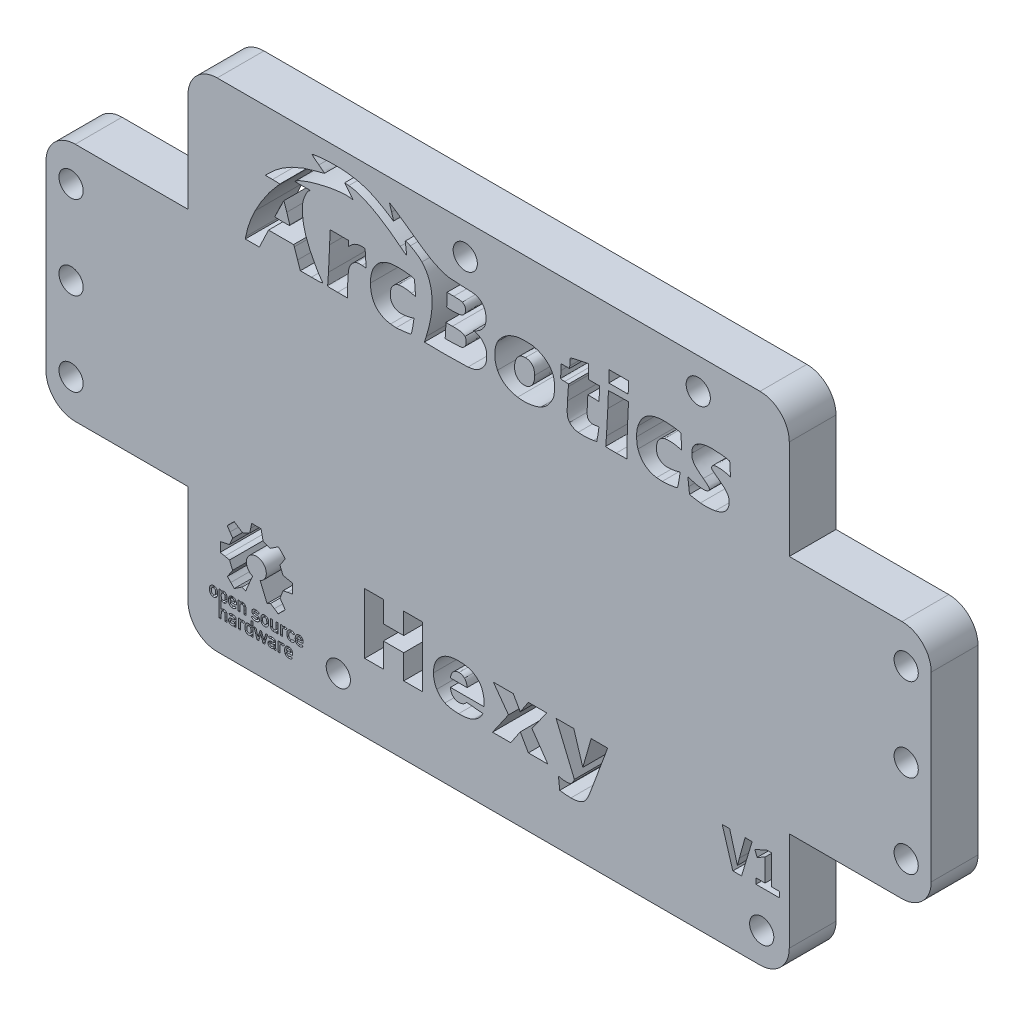
SolidWorks part; units mm, degrees
material "Acrylic (Medium-high impact)"
ref_plane "Front Plane" through (0, 0, 0) normal (0, 0, 1) x (1, 0, 0)
ref_plane "Top Plane" through (0, 0, 0) normal (0, 1, 0) x (1, 0, 0)
ref_plane "Right Plane" through (0, 0, 0) normal (1, 0, 0) x (0, 0, -1)
sketch "Model" plane through (0, 0, 0) normal (0, 0, 1) x (1, 0, 0)
  line L30 (636.4922, 464.2723) -> (653.4922, 464.2723)
  line L53 (653.4922, 464.2723) -> (653.4922, 435.5223)
  line L72 (564.4922, 435.5223) -> (636.4922, 435.5223) construction
  line L73 (564.4922, 464.2723) -> (636.4922, 464.2723) construction
  line L76 (653.4922, 435.5223) -> (636.4922, 435.5223)
  line L77 (636.4922, 435.5223) -> (636.4922, 420.1473)
  line L100 (636.4922, 420.1473) -> (564.4922, 420.1473)
  line L123 (564.4922, 420.1473) -> (564.4922, 435.5223)
  line L124 (564.4922, 435.5223) -> (547.4922, 435.5223)
  line L147 (547.4922, 435.5223) -> (547.4922, 464.2723)
  line L170 (547.4922, 464.2723) -> (564.4922, 464.2723)
  line L171 (564.4922, 464.2723) -> (564.4922, 479.6473)
  line L194 (564.4922, 479.6473) -> (636.4922, 479.6473)
  line L217 (636.4922, 479.6473) -> (636.4922, 464.2723)
  line L280 (585.6515, 435.5223) -> (587.8888, 435.5223)
  line L281 (587.8888, 435.5223) -> (587.8888, 432.9858)
  line L282 (587.8888, 432.9858) -> (590.3255, 432.9858)
  line L283 (590.3255, 432.9858) -> (590.3255, 435.5223)
  line L284 (590.3255, 435.5223) -> (592.5628, 435.5223)
  line L285 (592.5628, 435.5223) -> (592.5628, 428.2833)
  line L286 (592.5628, 428.2833) -> (590.3255, 428.2833)
  line L287 (590.3255, 428.2833) -> (590.3255, 431.2046)
  line L288 (590.3255, 431.2046) -> (587.8888, 431.2046)
  line L289 (587.8888, 431.2046) -> (587.8888, 428.2833)
  line L290 (587.8888, 428.2833) -> (585.6515, 428.2833)
  line L291 (585.6515, 428.2833) -> (585.6515, 435.5223)
  line L292 (599.9538, 430.4113) -> (595.921, 430.4113)
  line L293 (597.859, 429.8271) -> (599.8398, 429.6418)
  line L294 (599.9538, 430.6393) -> (599.9538, 430.4113)
  line L295 (595.921, 431.3803) -> (597.916, 431.3803)
  line L296 (601.0605, 433.5273) -> (603.4403, 433.5273)
  line L297 (603.4403, 433.5273) -> (604.281, 432.0596)
  line L298 (604.281, 432.0596) -> (605.25, 433.5273)
  line L299 (605.25, 433.5273) -> (607.4588, 433.5273)
  line L300 (607.4588, 433.5273) -> (605.6775, 431.0336)
  line L301 (605.6775, 431.0336) -> (607.587, 428.2833)
  line L302 (607.587, 428.2833) -> (605.25, 428.2833)
  line L303 (605.25, 428.2833) -> (604.281, 429.9791)
  line L304 (604.281, 429.9791) -> (603.141, 428.2833)
  line L305 (603.141, 428.2833) -> (600.9608, 428.2833)
  line L306 (600.9608, 428.2833) -> (602.8703, 431.0336)
  line L307 (602.8703, 431.0336) -> (601.0605, 433.5273)
  line L308 (608.5655, 433.5273) -> (610.6888, 433.5273)
  line L309 (610.6888, 433.5273) -> (611.7718, 430.0361)
  line L310 (611.7718, 430.0361) -> (612.7693, 433.5273)
  line L311 (612.7693, 433.5273) -> (614.75, 433.5273)
  line L312 (614.75, 433.5273) -> (612.6695, 427.9271)
  line L313 (609.0073, 426.2741) -> (608.8505, 427.6848)
  line L314 (610.76, 428.2833) -> (608.5655, 433.5273)
  line L497 (600.4922, -493.6423) -> (600.4922, 47006.3577) construction
  line L498 (-451.9635, 449.8973) -> (49548.0365, 449.8973) construction
  circle A0 centre (550.4922, 449.8973) radius 1.45
  circle A1 centre (550.4922, 459.8973) radius 1.45
  circle A2 centre (550.4922, 439.8973) radius 1.45
  circle A3 centre (650.4922, 439.8973) radius 1.45
  circle A4 centre (650.4922, 459.8973) radius 1.45
  circle A5 centre (650.4922, 449.8973) radius 1.45
  circle A6 centre (597.6922, 475.9473) radius 1.45
  circle A7 centre (625.5922, 475.9473) radius 1.45
  circle A8 centre (633.1922, 423.8473) radius 1.45
  circle A9 centre (582.4922, 425.1473) radius 1.45
  spline S335 degree 3 poles (595.921, 430.4113) (595.9495, 430.0978) (596.035, 429.8556) (596.1775, 429.6988) knots 0 0 0 0 1 1 1 1
  spline S336 degree 3 poles (596.1775, 429.6988) (596.377, 429.4708) (596.6335, 429.3568) (596.947, 429.3568) knots 0 0 0 0 1 1 1 1
  spline S337 degree 3 poles (596.947, 429.3568) (597.1465, 429.3568) (597.3318, 429.3996) (597.5028, 429.4993) knots 0 0 0 0 1 1 1 1
  spline S338 degree 3 poles (597.5028, 429.4993) (597.6168, 429.5563) (597.7308, 429.6703) (597.859, 429.8271) knots 0 0 0 0 1 1 1 1
  spline S339 degree 3 poles (599.8398, 429.6418) (599.5405, 429.1288) (599.17, 428.7441) (598.7425, 428.5161) knots 0 0 0 0 1 1 1 1
  spline S340 degree 3 poles (598.7425, 428.5161) (598.315, 428.2881) (597.7023, 428.1741) (596.9043, 428.1741) knots 0 0 0 0 1 1 1 1
  spline S341 degree 3 poles (596.9043, 428.1741) (596.2203, 428.1741) (595.6645, 428.2738) (595.2655, 428.4733) knots 0 0 0 0 1 1 1 1
  spline S342 degree 3 poles (595.2655, 428.4733) (594.8665, 428.6586) (594.5388, 428.9721) (594.2823, 429.3996) knots 0 0 0 0 1 1 1 1
  spline S343 degree 3 poles (594.2823, 429.3996) (594.0258, 429.8271) (593.8833, 430.3258) (593.8833, 430.8958) knots 0 0 0 0 1 1 1 1
  spline S344 degree 3 poles (593.8833, 430.8958) (593.8833, 431.7081) (594.1398, 432.3778) (594.667, 432.8908) knots 0 0 0 0 1 1 1 1
  spline S345 degree 3 poles (594.667, 432.8908) (595.18, 433.3896) (595.9068, 433.6461) (596.8473, 433.6461) knots 0 0 0 0 1 1 1 1
  spline S346 degree 3 poles (596.8473, 433.6461) (597.5883, 433.6461) (598.1868, 433.5321) (598.6143, 433.3041) knots 0 0 0 0 1 1 1 1
  spline S347 degree 3 poles (598.6143, 433.3041) (599.0418, 433.0761) (599.3838, 432.7483) (599.6118, 432.3208) knots 0 0 0 0 1 1 1 1
  spline S348 degree 3 poles (599.6118, 432.3208) (599.8398, 431.8933) (599.9538, 431.3376) (599.9538, 430.6393) knots 0 0 0 0 1 1 1 1
  spline S349 degree 3 poles (597.916, 431.3803) (597.8875, 431.7651) (597.7735, 432.0358) (597.6025, 432.2068) knots 0 0 0 0 1 1 1 1
  spline S350 degree 3 poles (597.6025, 432.2068) (597.4315, 432.3778) (597.2178, 432.4633) (596.9328, 432.4633) knots 0 0 0 0 1 1 1 1
  spline S351 degree 3 poles (596.9328, 432.4633) (596.6193, 432.4633) (596.3628, 432.3351) (596.1633, 432.0786) knots 0 0 0 0 1 1 1 1
  spline S352 degree 3 poles (596.1633, 432.0786) (596.0493, 431.9361) (595.9638, 431.6938) (595.921, 431.3803) knots 0 0 0 0 1 1 1 1
  spline S353 degree 3 poles (612.6695, 427.9271) (612.4415, 427.3001) (612.1993, 426.8583) (611.9428, 426.6303) knots 0 0 0 0 1 1 1 1
  spline S354 degree 3 poles (611.9428, 426.6303) (611.6008, 426.3168) (611.0593, 426.1601) (610.3468, 426.1601) knots 0 0 0 0 1 1 1 1
  spline S355 degree 3 poles (610.3468, 426.1601) (610.0618, 426.1601) (609.62, 426.1886) (609.0073, 426.2741) knots 0 0 0 0 1 1 1 1
  spline S356 degree 3 poles (608.8505, 427.6848) (609.1355, 427.5993) (609.449, 427.5423) (609.8195, 427.5423) knots 0 0 0 0 1 1 1 1
  spline S357 degree 3 poles (609.8195, 427.5423) (610.0475, 427.5423) (610.247, 427.5851) (610.3895, 427.6991) knots 0 0 0 0 1 1 1 1
  spline S358 degree 3 poles (610.3895, 427.6991) (610.532, 427.8131) (610.6603, 427.9983) (610.76, 428.2833) knots 0 0 0 0 1 1 1 1
  point P88 (653.4922, 449.8973)
  point P186 (600.4922, 435.5223)
  point P1129 (600.4922, 479.6473)
  point P1131 (600.4922, 420.1473)
  point P1133 (600.4922, 449.8973)
  point P1136 (547.4922, 449.8973)
  line B0 (613.0468, 464.5828) -> (613.4398, 464.6561)
  line B1 (613.4398, 464.6561) -> (613.5866, 465.4678)
  line B2 (612.3494, 468.6805) -> (612.3841, 468.9854)
  line B3 (612.3841, 468.9854) -> (613.0431, 468.9665)
  line B4 (613.0431, 468.9665) -> (613.702, 468.9476)
  line B5 (613.702, 468.9476) -> (613.7416, 469.5458)
  line B6 (613.7815, 470.3726) -> (613.7818, 470.6013)
  line B7 (613.7818, 470.6013) -> (613.104, 470.6013)
  line B8 (613.104, 470.6013) -> (612.4262, 470.6013)
  line B9 (612.4262, 470.6013) -> (612.4505, 471.4303)
  line B10 (612.4505, 471.4303) -> (612.4747, 472.2593)
  line B11 (612.4747, 472.2593) -> (612.2898, 472.2262)
  line B12 (610.2064, 470.8842) -> (610.1677, 470.6013)
  line B13 (610.1677, 470.6013) -> (609.6576, 470.6013)
  line B14 (609.6576, 470.6013) -> (609.1476, 470.6013)
  line B15 (609.1476, 470.6013) -> (609.1385, 469.8695)
  line B16 (609.5972, 468.9674) -> (610.0773, 468.9495)
  line B17 (610.0773, 468.9495) -> (610.0417, 468.6626)
  line B18 (629.2635, 469.038) -> (629.4705, 468.9537)
  line B19 (629.4705, 468.9537) -> (629.4316, 469.3659)
  line B20 (571.4078, 464.892) -> (571.358, 464.6256)
  line B21 (571.358, 464.6256) -> (572.2051, 464.6256)
  line B22 (572.2051, 464.6256) -> (573.0522, 464.6256)
  line B23 (573.0522, 464.6256) -> (573.1224, 464.7933)
  line B24 (573.6659, 465.9518) -> (574.1392, 466.9427)
  line B25 (574.1392, 466.9427) -> (575.6401, 466.9427)
  line B26 (575.6401, 466.9427) -> (577.1409, 466.9427)
  line B27 (577.1409, 466.9427) -> (577.2268, 466.7445)
  line B28 (577.6293, 465.586) -> (577.946, 464.6256)
  line B29 (577.946, 464.6256) -> (579.2783, 464.6256)
  line B30 (583.4807, 476.1434) -> (583.265, 476.411)
  line B31 (583.265, 476.411) -> (583.7519, 476.3661)
  line B32 (598.9104, 468.7408) -> (598.7037, 468.7854)
  line B33 (598.7037, 468.7854) -> (599.0698, 468.9611)
  line B34 (574.0883, 472.7703) -> (573.755, 472.4306)
  line B35 (573.755, 472.4306) -> (574.6219, 472.4306)
  line B36 (595.3267, 466.7695) -> (595.2871, 466.2609)
  line B37 (595.2871, 466.2609) -> (596.2569, 466.2817)
  line B38 (596.1632, 467.9793) -> (595.367, 467.9793)
  line B39 (595.367, 467.9793) -> (595.3666, 467.6287)
  line B40 (596.3182, 471.1699) -> (595.5194, 471.1805)
  line B41 (595.5194, 471.1805) -> (595.4882, 470.4183)
  line B42 (582.4095, 464.6256) -> (583.5985, 464.6256)
  line B43 (583.5985, 464.6256) -> (583.5996, 465.5555)
  line B44 (585.3449, 468.8801) -> (585.8119, 468.8501)
  line B45 (585.8119, 468.8501) -> (585.771, 469.7991)
  line B46 (583.9796, 470.2773) -> (583.7205, 470.0271)
  line B47 (583.7205, 470.0271) -> (583.7205, 470.3447)
  line B48 (583.7205, 470.3447) -> (583.7205, 470.6622)
  line B49 (583.7205, 470.6622) -> (582.6534, 470.6622)
  line B50 (615.7788, 464.6396) -> (617.0441, 464.6561)
  line B51 (617.0441, 464.6561) -> (617.0851, 466.9427)
  line B52 (617.2564, 470.5403) -> (617.2575, 470.6927)
  line B53 (617.2575, 470.6927) -> (616.061, 470.6801)
  line B54 (614.8794, 472.1562) -> (614.8794, 471.4549)
  line B55 (614.8794, 471.4549) -> (616.0297, 471.4549)
  line B56 (616.0297, 471.4549) -> (617.1799, 471.4549)
  line B57 (617.1799, 471.4549) -> (617.2187, 471.7378)
  line B58 (617.2575, 472.4391) -> (617.2575, 472.8574)
  line B59 (617.2575, 472.8574) -> (616.0685, 472.8574)
  line B60 (616.0685, 472.8574) -> (614.8794, 472.8574)
  line B61 (614.8794, 472.8574) -> (614.8794, 472.1562)
  spline B62 degree 3 poles (588.751, 464.5107) (588.9523, 464.4814) (589.2541, 464.4547) (589.4218, 464.4513) knots 0 0 0 0 1 1 1 1
  spline B63 degree 3 poles (589.4218, 464.4513) (589.7218, 464.4451) (590.9484, 464.589) (591.155, 464.6546) knots 0 0 0 0 1 1 1 1
  spline B64 degree 3 poles (591.155, 464.6546) (591.2389, 464.6812) (591.2926, 464.8736) (591.4151, 465.5868) knots 0 0 0 0 1 1 1 1
  spline B65 degree 3 poles (591.4151, 465.5868) (591.5, 466.081) (591.5652, 466.4911) (591.5601, 466.4981) knots 0 0 0 0 1 1 1 1
  spline B66 degree 3 poles (591.5601, 466.4981) (591.5549, 466.5052) (591.3821, 466.4584) (591.1761, 466.3943) knots 0 0 0 0 1 1 1 1
  spline B67 degree 3 poles (591.1761, 466.3943) (590.6782, 466.2394) (589.976, 466.1795) (589.6597, 466.2651) knots 0 0 0 0 1 1 1 1
  spline B68 degree 3 poles (589.6597, 466.2651) (589.0365, 466.4336) (588.7206, 466.8674) (588.7206, 467.5545) knots 0 0 0 0 1 1 1 1
  spline B69 degree 3 poles (588.7206, 467.5545) (588.7206, 467.7762) (588.7639, 468.0847) (588.8168, 468.24) knots 0 0 0 0 1 1 1 1
  spline B70 degree 3 poles (588.8168, 468.24) (588.936, 468.59) (589.2906, 468.9229) (589.647, 469.0196) knots 0 0 0 0 1 1 1 1
  spline B71 degree 3 poles (589.647, 469.0196) (590.0322, 469.1241) (590.6962, 469.098) (591.2459, 468.9568) knots 0 0 0 0 1 1 1 1
  spline B72 degree 3 poles (591.2459, 468.9568) (591.5114, 468.8886) (591.7328, 468.8397) (591.738, 468.8481) knots 0 0 0 0 1 1 1 1
  spline B73 degree 3 poles (591.738, 468.8481) (591.7579, 468.8806) (591.6354, 470.5721) (591.6114, 470.5964) knots 0 0 0 0 1 1 1 1
  spline B74 degree 3 poles (591.6114, 470.5964) (591.5974, 470.6105) (591.4146, 470.6594) (591.2051, 470.7051) knots 0 0 0 0 1 1 1 1
  spline B75 degree 3 poles (591.2051, 470.7051) (590.6128, 470.8343) (589.4589, 470.8749) (588.8692, 470.7871) knots 0 0 0 0 1 1 1 1
  spline B76 degree 3 poles (588.8692, 470.7871) (587.2787, 470.5505) (586.3406, 469.3476) (586.3434, 467.5485) knots 0 0 0 0 1 1 1 1
  spline B77 degree 3 poles (586.3434, 467.5485) (586.3461, 465.8019) (587.1897, 464.7374) (588.751, 464.5107) knots 0 0 0 0 1 1 1 1
  spline B78 degree 3 poles (603.9646, 464.5298) (604.8317, 464.3732) (606.0481, 464.5344) (606.7739, 464.9022) knots 0 0 0 0 1 1 1 1
  spline B79 degree 3 poles (606.7739, 464.9022) (607.4037, 465.2213) (607.9804, 465.8932) (608.2417, 466.6122) knots 0 0 0 0 1 1 1 1
  spline B80 degree 3 poles (608.2417, 466.6122) (608.4308, 467.1328) (608.4339, 468.3414) (608.2473, 468.8472) knots 0 0 0 0 1 1 1 1
  spline B81 degree 3 poles (608.2473, 468.8472) (607.9277, 469.7135) (607.2666, 470.3089) (606.2513, 470.6451) knots 0 0 0 0 1 1 1 1
  spline B82 degree 3 poles (606.2513, 470.6451) (605.8244, 470.7864) (605.6606, 470.8071) (604.9403, 470.8106) knots 0 0 0 0 1 1 1 1
  spline B83 degree 3 poles (604.9403, 470.8106) (604.0301, 470.8151) (603.5723, 470.7134) (602.8408, 470.3441) knots 0 0 0 0 1 1 1 1
  spline B84 degree 3 poles (602.8408, 470.3441) (602.3905, 470.1168) (601.7794, 469.5175) (601.5635, 469.0915) knots 0 0 0 0 1 1 1 1
  spline B85 degree 3 poles (601.5635, 469.0915) (601.1143, 468.2051) (601.1113, 467.0357) (601.5559, 466.1176) knots 0 0 0 0 1 1 1 1
  spline B86 degree 3 poles (601.5559, 466.1176) (601.9593, 465.2845) (602.7792, 464.744) (603.9646, 464.5298) knots 0 0 0 0 1 1 1 1
  spline B87 degree 3 poles (603.6624, 466.9903) (603.8399, 466.3513) (604.5661, 465.9923) (605.1709, 466.2445) knots 0 0 0 0 1 1 1 1
  spline B88 degree 3 poles (605.1709, 466.2445) (605.7256, 466.4759) (606.0076, 467.0019) (606.0029, 467.7963) knots 0 0 0 0 1 1 1 1
  spline B89 degree 3 poles (606.0029, 467.7963) (605.9979, 468.6361) (605.6122, 469.0856) (604.8956, 469.0866) knots 0 0 0 0 1 1 1 1
  spline B90 degree 3 poles (604.8956, 469.0866) (604.5085, 469.0872) (604.2405, 468.9745) (604.0026, 468.7112) knots 0 0 0 0 1 1 1 1
  spline B91 degree 3 poles (604.0026, 468.7112) (603.6511, 468.3222) (603.502, 467.5679) (603.6624, 466.9903) knots 0 0 0 0 1 1 1 1
  spline B92 degree 3 poles (613.5866, 465.4678) (613.6674, 465.9143) (613.7199, 466.2933) (613.7032, 466.31) knots 0 0 0 0 1 1 1 1
  spline B93 degree 3 poles (613.7032, 466.31) (613.6864, 466.3267) (613.5083, 466.3064) (613.3073, 466.2649) knots 0 0 0 0 1 1 1 1
  spline B94 degree 3 poles (613.3073, 466.2649) (612.8597, 466.1724) (612.5951, 466.235) (612.4161, 466.4758) knots 0 0 0 0 1 1 1 1
  spline B95 degree 3 poles (612.4161, 466.4758) (612.2983, 466.6342) (612.289, 466.7178) (612.3013, 467.5119) knots 0 0 0 0 1 1 1 1
  spline B96 degree 3 poles (612.3013, 467.5119) (612.3086, 467.9869) (612.3302, 468.5128) (612.3494, 468.6805) knots 0 0 0 0 1 1 1 1
  spline B97 degree 3 poles (613.7416, 469.5458) (613.7634, 469.8748) (613.7814, 470.2468) (613.7815, 470.3726) knots 0 0 0 0 1 1 1 1
  spline B98 degree 3 poles (612.2898, 472.2262) (611.9814, 472.1711) (610.403, 471.8233) (610.3214, 471.7924) knots 0 0 0 0 1 1 1 1
  spline B99 degree 3 poles (610.3214, 471.7924) (610.2748, 471.7748) (610.2452, 471.648) (610.2452, 471.4654) knots 0 0 0 0 1 1 1 1
  spline B100 degree 3 poles (610.2452, 471.4654) (610.2452, 471.3013) (610.2278, 471.0398) (610.2064, 470.8842) knots 0 0 0 0 1 1 1 1
  spline B101 degree 3 poles (609.1385, 469.8695) (609.1335, 469.4671) (609.1266, 469.1035) (609.1232, 469.0616) knots 0 0 0 0 1 1 1 1
  spline B102 degree 3 poles (609.1232, 469.0616) (609.119, 469.0079) (609.2592, 468.9801) (609.5972, 468.9674) knots 0 0 0 0 1 1 1 1
  spline B103 degree 3 poles (610.0417, 468.6626) (610.0221, 468.5047) (609.9737, 467.818) (609.934, 467.1365) knots 0 0 0 0 1 1 1 1
  spline B104 degree 3 poles (609.934, 467.1365) (609.8511, 465.7111) (609.8893, 465.399) (610.1919, 465.0319) knots 0 0 0 0 1 1 1 1
  spline B105 degree 3 poles (610.1919, 465.0319) (610.4256, 464.7483) (610.7584, 464.5756) (611.2081, 464.5046) knots 0 0 0 0 1 1 1 1
  spline B106 degree 3 poles (611.2081, 464.5046) (611.6129, 464.4406) (612.483, 464.4776) (613.0468, 464.5828) knots 0 0 0 0 1 1 1 1
  spline B107 degree 3 poles (620.6082, 464.5073) (620.7943, 464.4799) (621.0975, 464.4547) (621.2819, 464.4513) knots 0 0 0 0 1 1 1 1
  spline B108 degree 3 poles (621.2819, 464.4513) (621.6977, 464.4435) (622.8842, 464.5977) (623.0366, 464.6792) knots 0 0 0 0 1 1 1 1
  spline B109 degree 3 poles (623.0366, 464.6792) (623.1253, 464.7267) (623.1777, 464.912) (623.2835, 465.5515) knots 0 0 0 0 1 1 1 1
  spline B110 degree 3 poles (623.2835, 465.5515) (623.3573, 465.998) (623.4173, 466.3965) (623.4169, 466.4369) knots 0 0 0 0 1 1 1 1
  spline B111 degree 3 poles (623.4169, 466.4369) (623.4163, 466.492) (623.3538, 466.4885) (623.1676, 466.4228) knots 0 0 0 0 1 1 1 1
  spline B112 degree 3 poles (623.1676, 466.4228) (622.6866, 466.253) (621.9405, 466.1806) (621.5569, 466.2665) knots 0 0 0 0 1 1 1 1
  spline B113 degree 3 poles (621.5569, 466.2665) (621.1463, 466.3584) (620.7771, 466.6551) (620.6702, 466.9792) knots 0 0 0 0 1 1 1 1
  spline B114 degree 3 poles (620.6702, 466.9792) (620.5588, 467.3166) (620.5831, 467.9896) (620.7176, 468.2937) knots 0 0 0 0 1 1 1 1
  spline B115 degree 3 poles (620.7176, 468.2937) (620.8662, 468.6296) (621.206, 468.9296) (621.5403, 469.0202) knots 0 0 0 0 1 1 1 1
  spline B116 degree 3 poles (621.5403, 469.0202) (622.0074, 469.1466) (622.9549, 469.0685) (623.4985, 468.8587) knots 0 0 0 0 1 1 1 1
  spline B117 degree 3 poles (623.4985, 468.8587) (623.6063, 468.8171) (623.6093, 468.8543) (623.5673, 469.693) knots 0 0 0 0 1 1 1 1
  spline B118 degree 3 poles (623.5673, 469.693) (623.543, 470.1758) (623.5143, 470.5807) (623.5034, 470.5929) knots 0 0 0 0 1 1 1 1
  spline B119 degree 3 poles (623.5034, 470.5929) (623.4391, 470.6649) (622.6091, 470.7901) (621.9722, 470.8239) knots 0 0 0 0 1 1 1 1
  spline B120 degree 3 poles (621.9722, 470.8239) (619.973, 470.93) (618.8783, 470.2985) (618.3793, 468.7511) knots 0 0 0 0 1 1 1 1
  spline B121 degree 3 poles (618.3793, 468.7511) (618.2448, 468.3338) (618.2187, 468.1407) (618.2176, 467.5524) knots 0 0 0 0 1 1 1 1
  spline B122 degree 3 poles (618.2176, 467.5524) (618.2166, 466.9559) (618.2404, 466.7784) (618.3775, 466.3634) knots 0 0 0 0 1 1 1 1
  spline B123 degree 3 poles (618.3775, 466.3634) (618.7209, 465.324) (619.5077, 464.6694) (620.6082, 464.5073) knots 0 0 0 0 1 1 1 1
  spline B124 degree 3 poles (629.4316, 469.3659) (629.4102, 469.5926) (629.392, 469.9427) (629.3913, 470.1439) knots 0 0 0 0 1 1 1 1
  spline B125 degree 3 poles (629.3913, 470.1439) (629.3905, 470.3452) (629.3687, 470.5433) (629.3427, 470.5841) knots 0 0 0 0 1 1 1 1
  spline B126 degree 3 poles (629.3427, 470.5841) (629.3153, 470.6273) (628.9509, 470.7006) (628.4747, 470.7589) knots 0 0 0 0 1 1 1 1
  spline B127 degree 3 poles (628.4747, 470.7589) (626.0624, 471.0538) (624.8186, 470.5008) (624.8186, 469.1333) knots 0 0 0 0 1 1 1 1
  spline B128 degree 3 poles (624.8186, 469.1333) (624.8186, 468.4033) (625.0689, 468.054) (626.1985, 467.2082) knots 0 0 0 0 1 1 1 1
  spline B129 degree 3 poles (626.1985, 467.2082) (626.9069, 466.6777) (627.0148, 466.5282) (626.8597, 466.2914) knots 0 0 0 0 1 1 1 1
  spline B130 degree 3 poles (626.8597, 466.2914) (626.6739, 466.0079) (625.7177, 466.0195) (624.865, 466.3157) knots 0 0 0 0 1 1 1 1
  spline B131 degree 3 poles (624.865, 466.3157) (624.3442, 466.4967) (624.3328, 466.4979) (624.3589, 466.3711) knots 0 0 0 0 1 1 1 1
  spline B132 degree 3 poles (624.3589, 466.3711) (624.3737, 466.2998) (624.4171, 465.9122) (624.4556, 465.5097) knots 0 0 0 0 1 1 1 1
  spline B133 degree 3 poles (624.4556, 465.5097) (624.494, 465.1073) (624.5357, 464.7615) (624.5481, 464.7412) knots 0 0 0 0 1 1 1 1
  spline B134 degree 3 poles (624.5481, 464.7412) (624.5714, 464.7035) (625.1522, 464.5978) (625.8552, 464.5033) knots 0 0 0 0 1 1 1 1
  spline B135 degree 3 poles (625.8552, 464.5033) (626.324, 464.4403) (627.1683, 464.4727) (627.6278, 464.5712) knots 0 0 0 0 1 1 1 1
  spline B136 degree 3 poles (627.6278, 464.5712) (628.706, 464.8025) (629.2952, 465.4034) (629.2947, 466.2714) knots 0 0 0 0 1 1 1 1
  spline B137 degree 3 poles (629.2947, 466.2714) (629.2944, 466.9723) (629.0041, 467.3611) (627.8797, 468.1664) knots 0 0 0 0 1 1 1 1
  spline B138 degree 3 poles (627.8797, 468.1664) (627.5879, 468.3754) (627.3148, 468.5887) (627.2729, 468.6404) knots 0 0 0 0 1 1 1 1
  spline B139 degree 3 poles (627.2729, 468.6404) (627.1611, 468.7781) (627.1798, 468.9818) (627.3156, 469.1047) knots 0 0 0 0 1 1 1 1
  spline B140 degree 3 poles (627.3156, 469.1047) (627.5551, 469.3214) (628.6601, 469.2835) (629.2635, 469.038) knots 0 0 0 0 1 1 1 1
  spline B141 degree 3 poles (573.1224, 464.7933) (573.161, 464.8855) (573.4056, 465.4068) (573.6659, 465.9518) knots 0 0 0 0 1 1 1 1
  spline B142 degree 3 poles (577.2268, 466.7445) (577.274, 466.6355) (577.4551, 466.1142) (577.6293, 465.586) knots 0 0 0 0 1 1 1 1
  spline B143 degree 3 poles (579.2783, 464.6256) (580.735, 464.6256) (580.7483, 464.6294) (580.4612, 464.9635) knots 0 0 0 0 1 1 1 1
  spline B144 degree 3 poles (580.4612, 464.9635) (580.2053, 465.2614) (579.4153, 466.6377) (579.1153, 467.3085) knots 0 0 0 0 1 1 1 1
  spline B145 degree 3 poles (579.1153, 467.3085) (578.4572, 468.7799) (578.2157, 469.7455) (578.2078, 470.9366) knots 0 0 0 0 1 1 1 1
  spline B146 degree 3 poles (578.2078, 470.9366) (578.2029, 471.6707) (578.2221, 471.8544) (578.3448, 472.2476) knots 0 0 0 0 1 1 1 1
  spline B147 degree 3 poles (578.3448, 472.2476) (578.5066, 472.7668) (578.7996, 473.3175) (578.9708, 473.4244) knots 0 0 0 0 1 1 1 1
  spline B148 degree 3 poles (578.9708, 473.4244) (579.0343, 473.464) (579.0863, 473.5152) (579.0863, 473.5381) knots 0 0 0 0 1 1 1 1
  spline B149 degree 3 poles (579.0863, 473.5381) (579.0863, 473.5611) (578.6678, 473.5683) (578.1564, 473.5544) knots 0 0 0 0 1 1 1 1
  spline B150 degree 3 poles (578.1564, 473.5544) (577.3019, 473.531) (577.2364, 473.5367) (577.3485, 473.6249) knots 0 0 0 0 1 1 1 1
  spline B151 degree 3 poles (577.3485, 473.6249) (578.3291, 474.397) (582.5556, 475.4107) (583.846, 475.1834) knots 0 0 0 0 1 1 1 1
  spline B152 degree 3 poles (583.846, 475.1834) (584.0576, 475.1461) (584.2404, 475.1252) (584.2521, 475.137) knots 0 0 0 0 1 1 1 1
  spline B153 degree 3 poles (584.2521, 475.137) (584.2638, 475.1487) (584.1435, 475.3197) (583.9848, 475.517) knots 0 0 0 0 1 1 1 1
  spline B154 degree 3 poles (583.9848, 475.517) (583.8261, 475.7143) (583.5993, 475.9962) (583.4807, 476.1434) knots 0 0 0 0 1 1 1 1
  spline B155 degree 3 poles (583.7519, 476.3661) (585.2991, 476.2234) (587.5711, 475.0303) (589.9032, 473.1357) knots 0 0 0 0 1 1 1 1
  spline B156 degree 3 poles (589.9032, 473.1357) (590.3011, 472.8124) (590.6389, 472.5603) (590.654, 472.5753) knots 0 0 0 0 1 1 1 1
  spline B157 degree 3 poles (590.654, 472.5753) (590.6834, 472.6048) (590.5632, 473.7333) (590.5118, 473.9092) knots 0 0 0 0 1 1 1 1
  spline B158 degree 3 poles (590.5118, 473.9092) (590.4642, 474.0722) (590.6219, 474.0424) (591.1154, 473.7954) knots 0 0 0 0 1 1 1 1
  spline B159 degree 3 poles (591.1154, 473.7954) (591.6484, 473.5286) (592.2098, 473.1344) (592.5084, 472.8174) knots 0 0 0 0 1 1 1 1
  spline B160 degree 3 poles (592.5084, 472.8174) (593.9305, 471.3076) (594.1089, 468.6937) (593.0182, 465.3464) knots 0 0 0 0 1 1 1 1
  spline B161 degree 3 poles (593.0182, 465.3464) (592.9015, 464.9882) (592.806, 464.6795) (592.806, 464.6604) knots 0 0 0 0 1 1 1 1
  spline B162 degree 3 poles (592.806, 464.6604) (592.806, 464.6041) (597.4191, 464.6238) (598.0195, 464.6827) knots 0 0 0 0 1 1 1 1
  spline B163 degree 3 poles (598.0195, 464.6827) (598.7932, 464.7585) (599.2138, 464.9319) (599.6387, 465.3505) knots 0 0 0 0 1 1 1 1
  spline B164 degree 3 poles (599.6387, 465.3505) (600.0908, 465.7959) (600.2617, 466.2221) (600.2649, 466.9122) knots 0 0 0 0 1 1 1 1
  spline B165 degree 3 poles (600.2649, 466.9122) (600.2675, 467.4847) (600.1436, 467.8213) (599.7836, 468.2198) knots 0 0 0 0 1 1 1 1
  spline B166 degree 3 poles (599.7836, 468.2198) (599.5356, 468.4942) (599.2427, 468.669) (598.9104, 468.7408) knots 0 0 0 0 1 1 1 1
  spline B167 degree 3 poles (599.0698, 468.9611) (599.5315, 469.1827) (599.885, 469.5633) (600.0598, 470.0269) knots 0 0 0 0 1 1 1 1
  spline B168 degree 3 poles (600.0598, 470.0269) (600.2586, 470.5544) (600.2194, 471.3052) (599.9674, 471.7956) knots 0 0 0 0 1 1 1 1
  spline B169 degree 3 poles (599.9674, 471.7956) (599.7745, 472.1709) (599.3965, 472.4857) (598.9757, 472.6215) knots 0 0 0 0 1 1 1 1
  spline B170 degree 3 poles (598.9757, 472.6215) (598.8459, 472.6634) (598.1338, 472.711) (597.2877, 472.7343) knots 0 0 0 0 1 1 1 1
  spline B171 degree 3 poles (597.2877, 472.7343) (595.6821, 472.7786) (595.5355, 472.8052) (594.4218, 473.2547) knots 0 0 0 0 1 1 1 1
  spline B172 degree 3 poles (594.4218, 473.2547) (593.5737, 473.597) (593.0855, 473.9093) (590.6325, 475.6784) knots 0 0 0 0 1 1 1 1
  spline B173 degree 3 poles (590.6325, 475.6784) (589.6106, 476.4154) (588.6696, 477.0359) (588.6341, 476.9962) knots 0 0 0 0 1 1 1 1
  spline B174 degree 3 poles (588.6341, 476.9962) (588.6228, 476.9836) (588.7313, 476.6166) (588.8752, 476.1806) knots 0 0 0 0 1 1 1 1
  spline B175 degree 3 poles (588.8752, 476.1806) (589.0191, 475.7446) (589.1251, 475.376) (589.1107, 475.3615) knots 0 0 0 0 1 1 1 1
  spline B176 degree 3 poles (589.1107, 475.3615) (589.0962, 475.347) (589.0094, 475.3944) (588.9177, 475.467) knots 0 0 0 0 1 1 1 1
  spline B177 degree 3 poles (588.9177, 475.467) (588.5803, 475.734) (587.4253, 476.4083) (586.7564, 476.7288) knots 0 0 0 0 1 1 1 1
  spline B178 degree 3 poles (586.7564, 476.7288) (585.2711, 477.4404) (583.6743, 477.7262) (581.5863, 477.6542) knots 0 0 0 0 1 1 1 1
  spline B179 degree 3 poles (581.5863, 477.6542) (580.6299, 477.6212) (580.0011, 477.5614) (579.495, 477.4554) knots 0 0 0 0 1 1 1 1
  spline B180 degree 3 poles (579.495, 477.4554) (579.3478, 477.4246) (579.3353, 477.4063) (579.4035, 477.3229) knots 0 0 0 0 1 1 1 1
  spline B181 degree 3 poles (579.4035, 477.3229) (579.447, 477.2697) (579.7937, 476.9956) (580.1739, 476.7138) knots 0 0 0 0 1 1 1 1
  spline B182 degree 3 poles (580.1739, 476.7138) (580.5541, 476.4319) (580.8517, 476.1879) (580.8352, 476.1713) knots 0 0 0 0 1 1 1 1
  spline B183 degree 3 poles (580.8352, 476.1713) (580.8187, 476.1548) (580.4253, 476.0491) (579.961, 475.9364) knots 0 0 0 0 1 1 1 1
  spline B184 degree 3 poles (579.961, 475.9364) (577.4488, 475.3267) (575.6386, 474.3508) (574.0883, 472.7703) knots 0 0 0 0 1 1 1 1
  spline B185 degree 3 poles (574.6219, 472.4306) (575.0986, 472.4306) (575.4887, 472.4135) (575.4887, 472.3926) knots 0 0 0 0 1 1 1 1
  spline B186 degree 3 poles (575.4887, 472.3926) (575.4887, 472.3717) (575.3309, 472.1854) (575.1381, 471.9786) knots 0 0 0 0 1 1 1 1
  spline B187 degree 3 poles (575.1381, 471.9786) (574.2689, 471.0463) (573.1298, 469.3688) (572.5322, 468.141) knots 0 0 0 0 1 1 1 1
  spline B188 degree 3 poles (572.5322, 468.141) (571.9534, 466.9517) (571.604, 465.9422) (571.4078, 464.892) knots 0 0 0 0 1 1 1 1
  spline B189 degree 3 poles (596.2569, 466.2817) (597.0882, 466.2995) (597.2549, 466.3195) (597.4239, 466.4217) knots 0 0 0 0 1 1 1 1
  spline B190 degree 3 poles (597.4239, 466.4217) (597.8189, 466.6606) (597.9416, 467.321) (597.6544, 467.6623) knots 0 0 0 0 1 1 1 1
  spline B191 degree 3 poles (597.6544, 467.6623) (597.4469, 467.9089) (597.1159, 467.9793) (596.1632, 467.9793) knots 0 0 0 0 1 1 1 1
  spline B192 degree 3 poles (595.3666, 467.6287) (595.3664, 467.4358) (595.3484, 467.0492) (595.3267, 466.7695) knots 0 0 0 0 1 1 1 1
  spline B193 degree 3 poles (576.6801, 468.7567) (576.7182, 468.658) (576.6522, 468.65) (575.795, 468.65) knots 0 0 0 0 1 1 1 1
  spline B194 degree 3 poles (575.795, 468.65) (575.2856, 468.65) (574.8779, 468.6736) (574.8891, 468.7024) knots 0 0 0 0 1 1 1 1
  spline B195 degree 3 poles (574.8891, 468.7024) (574.9863, 468.9529) (575.948, 470.9059) (575.9736, 470.9049) knots 0 0 0 0 1 1 1 1
  spline B196 degree 3 poles (575.9736, 470.9049) (575.992, 470.9042) (576.1492, 470.4446) (576.323, 469.8835) knots 0 0 0 0 1 1 1 1
  spline B197 degree 3 poles (576.323, 469.8835) (576.4967, 469.3225) (576.6574, 468.8154) (576.6801, 468.7567) knots 0 0 0 0 1 1 1 1
  spline B198 degree 3 poles (595.4882, 470.4183) (595.471, 469.9991) (595.4679, 469.6321) (595.4813, 469.6027) knots 0 0 0 0 1 1 1 1
  spline B199 degree 3 poles (595.4813, 469.6027) (595.4947, 469.5733) (595.8654, 469.5618) (596.3052, 469.5771) knots 0 0 0 0 1 1 1 1
  spline B200 degree 3 poles (596.3052, 469.5771) (596.8946, 469.5976) (597.1567, 469.6321) (597.3024, 469.708) knots 0 0 0 0 1 1 1 1
  spline B201 degree 3 poles (597.3024, 469.708) (597.8642, 470.0011) (597.8846, 470.8386) (597.3355, 471.068) knots 0 0 0 0 1 1 1 1
  spline B202 degree 3 poles (597.3355, 471.068) (597.1849, 471.1309) (596.8686, 471.1626) (596.3182, 471.1699) knots 0 0 0 0 1 1 1 1
  spline B203 degree 3 poles (583.5996, 465.5555) (583.6008, 466.6301) (583.6819, 467.5231) (583.8147, 467.925) knots 0 0 0 0 1 1 1 1
  spline B204 degree 3 poles (583.8147, 467.925) (583.9421, 468.3107) (584.2723, 468.6788) (584.6047, 468.8057) knots 0 0 0 0 1 1 1 1
  spline B205 degree 3 poles (584.6047, 468.8057) (584.81, 468.8841) (584.9939, 468.9026) (585.3449, 468.8801) knots 0 0 0 0 1 1 1 1
  spline B206 degree 3 poles (585.771, 469.7991) (585.7433, 470.4398) (585.7057, 470.7649) (585.6552, 470.7998) knots 0 0 0 0 1 1 1 1
  spline B207 degree 3 poles (585.6552, 470.7998) (585.614, 470.8283) (585.4019, 470.8405) (585.1839, 470.827) knots 0 0 0 0 1 1 1 1
  spline B208 degree 3 poles (585.1839, 470.827) (584.7111, 470.7977) (584.346, 470.6311) (583.9796, 470.2773) knots 0 0 0 0 1 1 1 1
  spline B209 degree 3 poles (582.6534, 470.6622) (582.0665, 470.6622) (581.5657, 470.6691) (581.5406, 470.6775) knots 0 0 0 0 1 1 1 1
  spline B210 degree 3 poles (581.5406, 470.6775) (581.5154, 470.6859) (581.4763, 469.9656) (581.4536, 469.0769) knots 0 0 0 0 1 1 1 1
  spline B211 degree 3 poles (581.4536, 469.0769) (581.431, 468.1881) (581.3692, 466.8737) (581.3164, 466.156) knots 0 0 0 0 1 1 1 1
  spline B212 degree 3 poles (581.3164, 466.156) (581.2636, 465.4382) (581.2205, 464.8003) (581.2205, 464.7383) knots 0 0 0 0 1 1 1 1
  spline B213 degree 3 poles (581.2205, 464.7383) (581.2205, 464.6325) (581.2936, 464.6256) (582.4095, 464.6256) knots 0 0 0 0 1 1 1 1
  spline B214 degree 3 poles (617.0851, 466.9427) (617.1077, 468.2003) (617.1553, 469.49) (617.1908, 469.8086) knots 0 0 0 0 1 1 1 1
  spline B215 degree 3 poles (617.1908, 469.8086) (617.2263, 470.1272) (617.2558, 470.4564) (617.2564, 470.5403) knots 0 0 0 0 1 1 1 1
  spline B216 degree 3 poles (616.061, 470.6801) (615.4029, 470.6732) (614.857, 470.6595) (614.848, 470.6497) knots 0 0 0 0 1 1 1 1
  spline B217 degree 3 poles (614.848, 470.6497) (614.8389, 470.6398) (614.8, 469.7811) (614.7615, 468.7415) knots 0 0 0 0 1 1 1 1
  spline B218 degree 3 poles (614.7615, 468.7415) (614.723, 467.7018) (614.6515, 466.386) (614.6025, 465.8174) knots 0 0 0 0 1 1 1 1
  spline B219 degree 3 poles (614.6025, 465.8174) (614.5536, 465.2488) (614.5136, 464.7475) (614.5136, 464.7034) knots 0 0 0 0 1 1 1 1
  spline B220 degree 3 poles (614.5136, 464.7034) (614.5136, 464.639) (614.765, 464.6264) (615.7788, 464.6396) knots 0 0 0 0 1 1 1 1
  spline B221 degree 3 poles (617.2187, 471.7378) (617.24, 471.8934) (617.2575, 472.209) (617.2575, 472.4391) knots 0 0 0 0 1 1 1 1
  line B222 (572.6805, 435.5223) -> (572.6805, 426.8765) construction
  line B223 (569.4779, 431.9985) -> (569.8427, 432.8385)
  line B224 (571.0334, 434.0049) -> (571.8769, 434.371)
  line B225 (573.49, 434.3515) -> (574.3077, 434.03)
  line B226 (575.501, 432.879) -> (575.8699, 432.0026)
  line B227 (575.864, 430.3975) -> (575.5218, 429.4697)
  line B228 (569.4716, 430.3966) -> (569.8337, 429.5023)
  line B229 (577.0034, 431.7644) -> (577.0034, 430.6344)
  line B230 (573.1347, 430.0968) -> (573.9653, 428.1256)
  line B231 (572.2263, 430.0968) -> (571.3958, 428.1256)
  line B232 (570.9723, 428.3321) -> (571.3958, 428.1256)
  line B233 (573.9653, 428.1256) -> (574.3746, 428.3252)
  line B234 (573.2198, 424.9354) -> (573.2198, 423.6854) construction
  line B235 (573.093, 424.1801) -> (573.2198, 424.5818)
  line B236 (573.2198, 424.5818) -> (573.3467, 424.1802)
  line B237 (568.3576, 431.7644) -> (568.3576, 430.6344)
  line B238 (568.3576, 431.1994) -> (577.0034, 431.1994) construction
  line B239 (570.0018, 423.8327) -> (570.0506, 423.8801)
  line B240 (570.0506, 423.8801) -> (570.0506, 423.8256)
  line B241 (570.0506, 423.8256) -> (570.0506, 423.7711)
  line B242 (570.0506, 423.7711) -> (570.1612, 423.7711)
  line B243 (570.1612, 423.7711) -> (570.2717, 423.7711)
  line B244 (570.2717, 423.7711) -> (570.2716, 424.217)
  line B245 (569.4596, 424.8344) -> (569.3982, 424.7799)
  line B246 (569.3982, 424.7799) -> (569.4806, 424.7177)
  line B247 (570.0506, 424.5356) -> (570.0506, 424.4492)
  line B248 (570.0506, 424.4492) -> (569.8543, 424.4492)
  line B249 (570.0506, 424.1949) -> (570.0506, 424.2575)
  line B250 (570.0506, 424.2575) -> (569.8583, 424.2575)
  line B251 (571.9891, 423.8533) -> (572.0406, 423.8925)
  line B252 (572.0406, 423.8925) -> (572.0406, 423.8318)
  line B253 (572.0406, 423.8318) -> (572.0406, 423.7711)
  line B254 (572.0406, 423.7711) -> (572.1511, 423.7711)
  line B255 (572.1511, 423.7711) -> (572.2617, 423.7711)
  line B256 (572.2617, 423.7711) -> (572.2617, 424.5892)
  line B257 (572.2617, 424.5892) -> (572.2617, 425.4073)
  line B258 (572.2617, 425.4073) -> (572.1511, 425.4073)
  line B259 (572.1511, 425.4073) -> (572.0406, 425.4073)
  line B260 (572.0406, 425.4073) -> (572.0406, 425.1034)
  line B261 (572.0406, 425.1034) -> (572.0406, 424.7994)
  line B262 (572.0406, 424.7994) -> (571.9927, 424.8359)
  line B263 (574.7417, 423.841) -> (574.7822, 423.8798)
  line B264 (574.7822, 423.8798) -> (574.7822, 423.8255)
  line B265 (574.7822, 423.8255) -> (574.7822, 423.7711)
  line B266 (574.7822, 423.7711) -> (574.8936, 423.7711)
  line B267 (574.8936, 423.7711) -> (575.0049, 423.7711)
  line B268 (575.0049, 423.7711) -> (575.0004, 424.2329)
  line B269 (575.0004, 424.2329) -> (574.996, 424.6948)
  line B270 (574.996, 424.6948) -> (574.9512, 424.7671)
  line B271 (574.192, 424.8351) -> (574.1305, 424.7806)
  line B272 (574.1305, 424.7806) -> (574.2195, 424.7116)
  line B273 (574.7795, 424.5455) -> (574.7855, 424.4518)
  line B274 (574.7855, 424.4518) -> (574.5517, 424.4466)
  line B275 (574.7775, 424.1618) -> (574.7865, 424.2575)
  line B276 (574.7865, 424.2575) -> (574.589, 424.2575)
  line B277 (576.9334, 423.8826) -> (576.9939, 423.9373)
  line B278 (576.9939, 423.9373) -> (576.9323, 423.9905)
  line B279 (576.2959, 424.2023) -> (576.2876, 424.2575)
  line B280 (576.2876, 424.2575) -> (576.6552, 424.2575)
  line B281 (576.6552, 424.2575) -> (577.0227, 424.2575)
  line B282 (577.0227, 424.2575) -> (577.0227, 424.3797)
  line B283 (576.2941, 424.4897) -> (576.2852, 424.4492)
  line B284 (576.2852, 424.4492) -> (576.536, 424.4492)
  line B285 (576.536, 424.4492) -> (576.7869, 424.4492)
  line B286 (576.7869, 424.4492) -> (576.7866, 424.4971)
  line B287 (568.2376, 425.2746) -> (568.2376, 423.7711)
  line B288 (568.2376, 423.7711) -> (568.3555, 423.7711)
  line B289 (568.3555, 423.7711) -> (568.4734, 423.7711)
  line B290 (568.4734, 423.7711) -> (568.4734, 424.1558)
  line B291 (568.9423, 424.1581) -> (568.9469, 423.7711)
  line B292 (568.9469, 423.7711) -> (569.0574, 423.7711)
  line B293 (569.0574, 423.7711) -> (569.1678, 423.7711)
  line B294 (569.1678, 423.7711) -> (569.1633, 424.217)
  line B295 (568.514, 424.8425) -> (568.4734, 424.8043)
  line B296 (568.4734, 424.8043) -> (568.4734, 425.2697)
  line B297 (568.4734, 425.2697) -> (568.4734, 425.7351)
  line B298 (568.4734, 425.7351) -> (568.5268, 425.6944)
  line B299 (568.5479, 426.7123) -> (568.4734, 426.6622)
  line B300 (568.4734, 426.6622) -> (568.4734, 426.7201)
  line B301 (568.4734, 426.7201) -> (568.4734, 426.7781)
  line B302 (568.4734, 426.7781) -> (568.3555, 426.7781)
  line B303 (568.3555, 426.7781) -> (568.2376, 426.7781)
  line B304 (568.2376, 426.7781) -> (568.2376, 425.2746)
  line B305 (570.5371, 424.3534) -> (570.5371, 423.7711)
  line B306 (570.5371, 423.7711) -> (570.655, 423.7711)
  line B307 (570.655, 423.7711) -> (570.7729, 423.7711)
  line B308 (570.7729, 423.7711) -> (570.7729, 424.1581)
  line B309 (571.1047, 424.6913) -> (571.1605, 424.6648)
  line B310 (571.1605, 424.6648) -> (571.1959, 424.7081)
  line B311 (571.2747, 424.805) -> (571.3182, 424.8586)
  line B312 (571.3182, 424.8586) -> (571.2851, 424.8792)
  line B313 (570.8271, 424.8475) -> (570.7729, 424.7999)
  line B314 (570.7729, 424.7999) -> (570.7729, 424.8677)
  line B315 (570.7729, 424.8677) -> (570.7729, 424.9356)
  line B316 (570.7729, 424.9356) -> (570.655, 424.9356)
  line B317 (570.655, 424.9356) -> (570.5371, 424.9356)
  line B318 (570.5371, 424.9356) -> (570.5371, 424.3534)
  line B319 (572.6159, 424.2459) -> (572.7685, 423.7699)
  line B320 (572.7685, 423.7699) -> (572.8711, 423.7742)
  line B321 (572.8711, 423.7742) -> (572.9737, 423.7785)
  line B322 (572.9737, 423.7785) -> (573.093, 424.1801)
  line B323 (573.3467, 424.1802) -> (573.4658, 423.7785)
  line B324 (573.4658, 423.7785) -> (573.5697, 423.7742)
  line B325 (573.5697, 423.7742) -> (573.6737, 423.7699)
  line B326 (573.6737, 423.7699) -> (573.6969, 423.8479)
  line B327 (573.881, 424.4271) -> (574.042, 424.9282)
  line B328 (574.042, 424.9282) -> (573.9384, 424.9326)
  line B329 (573.4335, 424.5228) -> (573.3008, 424.9355)
  line B330 (573.3008, 424.9355) -> (573.2198, 424.9354)
  line B331 (573.2198, 424.9354) -> (573.1387, 424.9353)
  line B332 (573.1387, 424.9353) -> (573.0065, 424.5235)
  line B333 (572.7479, 424.5274) -> (572.6371, 424.9282)
  line B334 (572.6371, 424.9282) -> (572.5167, 424.9325)
  line B335 (572.5167, 424.9325) -> (572.3962, 424.9368)
  line B336 (572.3962, 424.9368) -> (572.4298, 424.8293)
  line B337 (575.2686, 424.3534) -> (575.2686, 423.7711)
  line B338 (575.2686, 423.7711) -> (575.3866, 423.7711)
  line B339 (575.3866, 423.7711) -> (575.5045, 423.7711)
  line B340 (575.5045, 423.7711) -> (575.5045, 424.1669)
  line B341 (575.9752, 424.7691) -> (576.0514, 424.8606)
  line B342 (576.0514, 424.8606) -> (575.9774, 424.8981)
  line B343 (575.5524, 424.8435) -> (575.5045, 424.7971)
  line B344 (575.5045, 424.7971) -> (575.5045, 424.8664)
  line B345 (575.5045, 424.8664) -> (575.5045, 424.9356)
  line B346 (575.5045, 424.9356) -> (575.3866, 424.9356)
  line B347 (575.3866, 424.9356) -> (575.2686, 424.9356)
  line B348 (575.2686, 424.9356) -> (575.2686, 424.3534)
  line B349 (569.5642, 426.0655) -> (569.5642, 426.1148)
  line B350 (569.5642, 426.1148) -> (569.9253, 426.1148)
  line B351 (569.9253, 426.1148) -> (570.2865, 426.1148)
  line B352 (570.2865, 426.1148) -> (570.2865, 426.2617)
  line B353 (569.5642, 426.3328) -> (569.5642, 426.2917)
  line B354 (569.5642, 426.2917) -> (569.8167, 426.2917)
  line B355 (569.8167, 426.2917) -> (570.0691, 426.2917)
  line B356 (570.0691, 426.2917) -> (570.0591, 426.3543)
  line B357 (572.8096, 426.5185) -> (572.8933, 426.4726)
  line B358 (572.8933, 426.4726) -> (572.9631, 426.5534)
  line B359 (572.9631, 426.5534) -> (573.033, 426.6343)
  line B360 (573.033, 426.6343) -> (572.9974, 426.662)
  line B361 (572.2902, 425.9108) -> (572.2282, 425.9557)
  line B362 (572.2282, 425.9557) -> (572.1546, 425.8821)
  line B363 (573.2126, 426.1956) -> (573.2124, 425.9594)
  line B364 (573.2124, 425.9594) -> (573.261, 425.8608)
  line B365 (575.0054, 425.6872) -> (575.0623, 425.733)
  line B366 (575.0623, 425.733) -> (575.0623, 425.6733)
  line B367 (575.0623, 425.6733) -> (575.0623, 425.6136)
  line B368 (575.0623, 425.6136) -> (575.1802, 425.6136)
  line B369 (575.1802, 425.6136) -> (575.2981, 425.6136)
  line B370 (575.2981, 425.6136) -> (575.2981, 426.1959)
  line B371 (575.2981, 426.1959) -> (575.2981, 426.7781)
  line B372 (575.2981, 426.7781) -> (575.1802, 426.7781)
  line B373 (575.1802, 426.7781) -> (575.0623, 426.7781)
  line B374 (575.0623, 426.7781) -> (575.0623, 426.3868)
  line B375 (574.5906, 426.4324) -> (574.5906, 426.7781)
  line B376 (574.5906, 426.7781) -> (574.4793, 426.7781)
  line B377 (574.4793, 426.7781) -> (574.3679, 426.7781)
  line B378 (574.3679, 426.7781) -> (574.3724, 426.3322)
  line B379 (574.3724, 426.3322) -> (574.3769, 425.8863)
  line B380 (574.3769, 425.8863) -> (574.4223, 425.8053)
  line B381 (577.1983, 425.7395) -> (577.2598, 425.795)
  line B382 (577.2598, 425.795) -> (577.2186, 425.8383)
  line B383 (577.2186, 426.5534) -> (577.2598, 426.5967)
  line B384 (577.2598, 426.5967) -> (577.1983, 426.6523)
  line B385 (578.2083, 425.7326) -> (578.2649, 425.7823)
  line B386 (578.2649, 425.7823) -> (578.1856, 425.8522)
  line B387 (577.5714, 426.0417) -> (577.5644, 426.1148)
  line B388 (577.5644, 426.1148) -> (577.92, 426.1148)
  line B389 (577.92, 426.1148) -> (578.2756, 426.1148)
  line B390 (578.2756, 426.1148) -> (578.2755, 426.2806)
  line B391 (577.5681, 426.341) -> (577.5681, 426.2917)
  line B392 (577.5681, 426.2917) -> (577.8183, 426.2917)
  line B393 (577.8183, 426.2917) -> (578.0685, 426.2917)
  line B394 (578.0685, 426.2917) -> (578.0602, 426.3396)
  line B395 (570.5076, 426.1959) -> (570.5076, 425.6136)
  line B396 (570.5076, 425.6136) -> (570.6181, 425.6136)
  line B397 (570.6181, 425.6136) -> (570.7287, 425.6136)
  line B398 (570.7287, 425.6136) -> (570.729, 425.9932)
  line B399 (571.2, 425.9932) -> (571.2004, 425.6136)
  line B400 (571.2004, 425.6136) -> (571.3109, 425.6136)
  line B401 (571.3109, 425.6136) -> (571.4215, 425.6136)
  line B402 (571.4215, 425.6136) -> (571.4213, 426.0522)
  line B403 (570.7766, 426.6851) -> (570.7287, 426.6397)
  line B404 (570.7287, 426.6397) -> (570.7287, 426.7089)
  line B405 (570.7287, 426.7089) -> (570.7287, 426.7781)
  line B406 (570.7287, 426.7781) -> (570.6181, 426.7781)
  line B407 (570.6181, 426.7781) -> (570.5076, 426.7781)
  line B408 (570.5076, 426.7781) -> (570.5076, 426.1959)
  line B409 (575.7872, 426.0079) -> (575.7824, 425.6136)
  line B410 (575.7824, 425.6136) -> (575.6729, 425.6136)
  line B411 (575.6729, 425.6136) -> (575.5635, 425.6136)
  line B412 (575.5635, 425.6136) -> (575.5635, 426.1959)
  line B413 (575.5635, 426.1959) -> (575.5635, 426.7781)
  line B414 (575.5635, 426.7781) -> (575.674, 426.7781)
  line B415 (575.674, 426.7781) -> (575.7846, 426.7781)
  line B416 (575.7846, 426.7781) -> (575.7846, 426.7192)
  line B417 (573.2459, 435.5223) -> (572.1151, 435.5223)
  arc B418 (572.2263, 430.0968) -> (573.1347, 430.0968) centre (572.6805, 431.1994) cw
  circle B419 centre (572.6805, 431.1994) radius 4.3229 construction
  circle B420 centre (572.6805, 431.1994) radius 3.2299 construction
  spline B421 degree 3 poles (570.2716, 424.217) (570.2715, 424.6573) (570.271, 424.6639) (570.2359, 424.7393) knots 0 0 0 0 1 1 1 1
  spline B422 degree 3 poles (570.2359, 424.7393) (570.1726, 424.8752) (570.0386, 424.9356) (569.8003, 424.9356) knots 0 0 0 0 1 1 1 1
  spline B423 degree 3 poles (569.8003, 424.9356) (569.6294, 424.9356) (569.5456, 424.9107) (569.4596, 424.8344) knots 0 0 0 0 1 1 1 1
  spline B424 degree 3 poles (569.4806, 424.7177) (569.5259, 424.6835) (569.5668, 424.6555) (569.5715, 424.6555) knots 0 0 0 0 1 1 1 1
  spline B425 degree 3 poles (569.5715, 424.6555) (569.5763, 424.6555) (569.5994, 424.6698) (569.6229, 424.6872) knots 0 0 0 0 1 1 1 1
  spline B426 degree 3 poles (569.6229, 424.6872) (569.6546, 424.7106) (569.6942, 424.7206) (569.7751, 424.7258) knots 0 0 0 0 1 1 1 1
  spline B427 degree 3 poles (569.7751, 424.7258) (569.975, 424.7387) (570.0506, 424.6864) (570.0506, 424.5356) knots 0 0 0 0 1 1 1 1
  spline B428 degree 3 poles (569.8543, 424.4492) (569.6041, 424.4492) (569.5224, 424.4274) (569.4361, 424.3378) knots 0 0 0 0 1 1 1 1
  spline B429 degree 3 poles (569.4361, 424.3378) (569.3344, 424.2321) (569.314, 424.086) (569.3818, 423.9499) knots 0 0 0 0 1 1 1 1
  spline B430 degree 3 poles (569.3818, 423.9499) (569.4225, 423.8682) (569.4881, 423.8137) (569.5893, 423.7776) knots 0 0 0 0 1 1 1 1
  spline B431 degree 3 poles (569.5893, 423.7776) (569.6554, 423.7541) (569.8306, 423.7503) (569.9024, 423.7709) knots 0 0 0 0 1 1 1 1
  spline B432 degree 3 poles (569.9024, 423.7709) (569.9302, 423.7788) (569.9749, 423.8067) (570.0018, 423.8327) knots 0 0 0 0 1 1 1 1
  spline B433 degree 3 poles (569.8583, 424.2575) (569.6367, 424.2575) (569.591, 424.243) (569.565, 424.1641) knots 0 0 0 0 1 1 1 1
  spline B434 degree 3 poles (569.565, 424.1641) (569.5372, 424.0799) (569.5875, 424.0014) (569.6852, 423.9763) knots 0 0 0 0 1 1 1 1
  spline B435 degree 3 poles (569.6852, 423.9763) (569.7575, 423.9578) (569.9435, 423.9715) (569.9845, 423.9984) knots 0 0 0 0 1 1 1 1
  spline B436 degree 3 poles (569.9845, 423.9984) (570.0243, 424.0244) (570.0504, 424.1023) (570.0506, 424.1949) knots 0 0 0 0 1 1 1 1
  spline B437 degree 3 poles (571.9927, 424.8359) (571.8952, 424.9101) (571.8259, 424.9356) (571.7215, 424.9356) knots 0 0 0 0 1 1 1 1
  spline B438 degree 3 poles (571.7215, 424.9356) (571.5977, 424.9356) (571.5179, 424.8996) (571.4364, 424.807) knots 0 0 0 0 1 1 1 1
  spline B439 degree 3 poles (571.4364, 424.807) (571.3504, 424.7093) (571.3404, 424.6606) (571.3409, 424.3386) knots 0 0 0 0 1 1 1 1
  spline B440 degree 3 poles (571.3409, 424.3386) (571.3413, 424.0772) (571.3436, 424.0534) (571.3759, 423.9811) knots 0 0 0 0 1 1 1 1
  spline B441 degree 3 poles (571.3759, 423.9811) (571.4143, 423.8949) (571.4848, 423.8254) (571.5753, 423.7842) knots 0 0 0 0 1 1 1 1
  spline B442 degree 3 poles (571.5753, 423.7842) (571.6983, 423.7284) (571.8609, 423.7555) (571.9891, 423.8533) knots 0 0 0 0 1 1 1 1
  spline B443 degree 3 poles (571.711, 423.9918) (571.7685, 423.9735) (571.889, 423.9861) (571.9333, 424.0151) knots 0 0 0 0 1 1 1 1
  spline B444 degree 3 poles (571.9333, 424.0151) (571.9834, 424.048) (572.0207, 424.1423) (572.032, 424.2649) knots 0 0 0 0 1 1 1 1
  spline B445 degree 3 poles (572.032, 424.2649) (572.0432, 424.3857) (572.0199, 424.5735) (571.9878, 424.6226) knots 0 0 0 0 1 1 1 1
  spline B446 degree 3 poles (571.9878, 424.6226) (571.9265, 424.7161) (571.7666, 424.7454) (571.6705, 424.6808) knots 0 0 0 0 1 1 1 1
  spline B447 degree 3 poles (571.6705, 424.6808) (571.5909, 424.6272) (571.5768, 424.5831) (571.5713, 424.3697) knots 0 0 0 0 1 1 1 1
  spline B448 degree 3 poles (571.5713, 424.3697) (571.5648, 424.115) (571.5968, 424.0283) (571.711, 423.9918) knots 0 0 0 0 1 1 1 1
  spline B449 degree 3 poles (574.9512, 424.7671) (574.917, 424.8223) (574.8861, 424.8498) (574.8197, 424.8838) knots 0 0 0 0 1 1 1 1
  spline B450 degree 3 poles (574.8197, 424.8838) (574.7412, 424.9239) (574.7168, 424.9287) (574.567, 424.9334) knots 0 0 0 0 1 1 1 1
  spline B451 degree 3 poles (574.567, 424.9334) (574.3694, 424.9397) (574.2849, 424.9175) (574.192, 424.8351) knots 0 0 0 0 1 1 1 1
  spline B452 degree 3 poles (574.2195, 424.7116) (574.2989, 424.6499) (574.3104, 424.645) (574.3279, 424.666) knots 0 0 0 0 1 1 1 1
  spline B453 degree 3 poles (574.3279, 424.666) (574.3969, 424.7493) (574.6719, 424.7515) (574.7462, 424.6694) knots 0 0 0 0 1 1 1 1
  spline B454 degree 3 poles (574.7462, 424.6694) (574.7649, 424.6487) (574.7754, 424.6096) (574.7795, 424.5455) knots 0 0 0 0 1 1 1 1
  spline B455 degree 3 poles (574.5517, 424.4466) (574.3469, 424.442) (574.3106, 424.4375) (574.259, 424.4098) knots 0 0 0 0 1 1 1 1
  spline B456 degree 3 poles (574.259, 424.4098) (574.1374, 424.3446) (574.0746, 424.2414) (574.0748, 424.1069) knots 0 0 0 0 1 1 1 1
  spline B457 degree 3 poles (574.0748, 424.1069) (574.0751, 423.9515) (574.1629, 423.834) (574.3209, 423.7776) knots 0 0 0 0 1 1 1 1
  spline B458 degree 3 poles (574.3209, 423.7776) (574.3983, 423.75) (574.5785, 423.7509) (574.6464, 423.7793) knots 0 0 0 0 1 1 1 1
  spline B459 degree 3 poles (574.6464, 423.7793) (574.6765, 423.7919) (574.7194, 423.8196) (574.7417, 423.841) knots 0 0 0 0 1 1 1 1
  spline B460 degree 3 poles (574.589, 424.2575) (574.4194, 424.2574) (574.385, 424.2534) (574.3445, 424.2287) knots 0 0 0 0 1 1 1 1
  spline B461 degree 3 poles (574.3445, 424.2287) (574.2849, 424.1924) (574.2675, 424.1201) (574.3022, 424.053) knots 0 0 0 0 1 1 1 1
  spline B462 degree 3 poles (574.3022, 424.053) (574.3153, 424.0277) (574.3275, 424.0069) (574.3293, 424.0067) knots 0 0 0 0 1 1 1 1
  spline B463 degree 3 poles (574.3293, 424.0067) (574.3312, 424.0066) (574.3592, 423.9965) (574.3916, 423.9843) knots 0 0 0 0 1 1 1 1
  spline B464 degree 3 poles (574.3916, 423.9843) (574.4571, 423.9596) (574.6568, 423.9645) (574.7083, 423.9921) knots 0 0 0 0 1 1 1 1
  spline B465 degree 3 poles (574.7083, 423.9921) (574.7512, 424.0151) (574.7676, 424.0552) (574.7775, 424.1618) knots 0 0 0 0 1 1 1 1
  spline B466 degree 3 poles (576.9323, 423.9905) (576.8386, 424.0717) (576.8352, 424.0726) (576.7731, 424.0315) knots 0 0 0 0 1 1 1 1
  spline B467 degree 3 poles (576.7731, 424.0315) (576.5698, 423.8969) (576.3291, 423.9831) (576.2959, 424.2023) knots 0 0 0 0 1 1 1 1
  spline B468 degree 3 poles (577.0227, 424.3797) (577.0227, 424.7254) (576.8632, 424.9174) (576.5635, 424.9326) knots 0 0 0 0 1 1 1 1
  spline B469 degree 3 poles (576.5635, 424.9326) (576.4509, 424.9383) (576.4266, 424.9348) (576.3559, 424.9024) knots 0 0 0 0 1 1 1 1
  spline B470 degree 3 poles (576.3559, 424.9024) (576.2121, 424.8366) (576.1289, 424.7272) (576.0869, 424.5491) knots 0 0 0 0 1 1 1 1
  spline B471 degree 3 poles (576.0869, 424.5491) (576.0466, 424.3784) (576.0672, 424.1325) (576.1326, 424.0025) knots 0 0 0 0 1 1 1 1
  spline B472 degree 3 poles (576.1326, 424.0025) (576.1843, 423.8997) (576.2851, 423.8178) (576.411, 423.7762) knots 0 0 0 0 1 1 1 1
  spline B473 degree 3 poles (576.411, 423.7762) (576.4482, 423.7639) (576.519, 423.7586) (576.6026, 423.7617) knots 0 0 0 0 1 1 1 1
  spline B474 degree 3 poles (576.6026, 423.7617) (576.7563, 423.7675) (576.8398, 423.7981) (576.9334, 423.8826) knots 0 0 0 0 1 1 1 1
  spline B475 degree 3 poles (576.7866, 424.4971) (576.7864, 424.5545) (576.7348, 424.6495) (576.6834, 424.6877) knots 0 0 0 0 1 1 1 1
  spline B476 degree 3 poles (576.6834, 424.6877) (576.6013, 424.7485) (576.463, 424.7398) (576.3821, 424.6688) knots 0 0 0 0 1 1 1 1
  spline B477 degree 3 poles (576.3821, 424.6688) (576.335, 424.6275) (576.3161, 424.589) (576.2941, 424.4897) knots 0 0 0 0 1 1 1 1
  spline B478 degree 3 poles (568.4734, 424.1558) (568.4734, 424.5819) (568.4787, 424.611) (568.5674, 424.6742) knots 0 0 0 0 1 1 1 1
  spline B479 degree 3 poles (568.5674, 424.6742) (568.6031, 424.6997) (568.6339, 424.7071) (568.7045, 424.7071) knots 0 0 0 0 1 1 1 1
  spline B480 degree 3 poles (568.7045, 424.7071) (568.808, 424.7071) (568.8586, 424.6793) (568.9083, 424.595) knots 0 0 0 0 1 1 1 1
  spline B481 degree 3 poles (568.9083, 424.595) (568.9354, 424.549) (568.9381, 424.5137) (568.9423, 424.1581) knots 0 0 0 0 1 1 1 1
  spline B482 degree 3 poles (569.1633, 424.217) (569.1591, 424.6418) (569.1573, 424.6657) (569.1269, 424.7226) knots 0 0 0 0 1 1 1 1
  spline B483 degree 3 poles (569.1269, 424.7226) (569.0503, 424.8657) (568.9358, 424.9349) (568.7756, 424.9349) knots 0 0 0 0 1 1 1 1
  spline B484 degree 3 poles (568.7756, 424.9349) (568.662, 424.9349) (568.5823, 424.9068) (568.514, 424.8425) knots 0 0 0 0 1 1 1 1
  spline B485 degree 3 poles (568.5268, 425.6944) (568.5932, 425.6437) (568.7088, 425.5989) (568.7731, 425.5989) knots 0 0 0 0 1 1 1 1
  spline B486 degree 3 poles (568.7731, 425.5989) (568.915, 425.5989) (569.0622, 425.69) (569.1244, 425.8164) knots 0 0 0 0 1 1 1 1
  spline B487 degree 3 poles (569.1244, 425.8164) (569.1572, 425.883) (569.1589, 425.9012) (569.1589, 426.1959) knots 0 0 0 0 1 1 1 1
  spline B488 degree 3 poles (569.1589, 426.1959) (569.1589, 426.4906) (569.1572, 426.5088) (569.1244, 426.5754) knots 0 0 0 0 1 1 1 1
  spline B489 degree 3 poles (569.1244, 426.5754) (569.0803, 426.665) (568.9885, 426.7434) (568.8952, 426.7711) knots 0 0 0 0 1 1 1 1
  spline B490 degree 3 poles (568.8952, 426.7711) (568.7635, 426.8102) (568.6698, 426.7943) (568.5479, 426.7123) knots 0 0 0 0 1 1 1 1
  spline B491 degree 3 poles (568.6968, 425.8348) (568.7623, 425.8348) (568.804, 425.8431) (568.8358, 425.8625) knots 0 0 0 0 1 1 1 1
  spline B492 degree 3 poles (568.8358, 425.8625) (568.9166, 425.9118) (568.9369, 425.9788) (568.9369, 426.1959) knots 0 0 0 0 1 1 1 1
  spline B493 degree 3 poles (568.9369, 426.1959) (568.9369, 426.3539) (568.932, 426.3975) (568.909, 426.4445) knots 0 0 0 0 1 1 1 1
  spline B494 degree 3 poles (568.909, 426.4445) (568.8693, 426.5258) (568.8106, 426.5569) (568.6968, 426.557) knots 0 0 0 0 1 1 1 1
  spline B495 degree 3 poles (568.6968, 426.557) (568.6105, 426.557) (568.5993, 426.5532) (568.5546, 426.5084) knots 0 0 0 0 1 1 1 1
  spline B496 degree 3 poles (568.5546, 426.5084) (568.4915, 426.4453) (568.4736, 426.3763) (568.4736, 426.1959) knots 0 0 0 0 1 1 1 1
  spline B497 degree 3 poles (568.4736, 426.1959) (568.4736, 426.0154) (568.4915, 425.9464) (568.5546, 425.8833) knots 0 0 0 0 1 1 1 1
  spline B498 degree 3 poles (568.5546, 425.8833) (568.5993, 425.8386) (568.6105, 425.8347) (568.6968, 425.8348) knots 0 0 0 0 1 1 1 1
  spline B499 degree 3 poles (570.7729, 424.1581) (570.773, 424.5819) (570.7783, 424.6122) (570.8639, 424.675) knots 0 0 0 0 1 1 1 1
  spline B500 degree 3 poles (570.8639, 424.675) (570.9206, 424.7165) (571.0352, 424.7243) (571.1047, 424.6913) knots 0 0 0 0 1 1 1 1
  spline B501 degree 3 poles (571.1959, 424.7081) (571.2154, 424.7319) (571.2509, 424.7755) (571.2747, 424.805) knots 0 0 0 0 1 1 1 1
  spline B502 degree 3 poles (571.2851, 424.8792) (571.2157, 424.9224) (571.1664, 424.9356) (571.0739, 424.9356) knots 0 0 0 0 1 1 1 1
  spline B503 degree 3 poles (571.0739, 424.9356) (570.9633, 424.9356) (570.9029, 424.914) (570.8271, 424.8475) knots 0 0 0 0 1 1 1 1
  spline B504 degree 3 poles (573.6969, 423.8479) (573.7096, 423.8908) (573.7925, 424.1514) (573.881, 424.4271) knots 0 0 0 0 1 1 1 1
  spline B505 degree 3 poles (573.9384, 424.9326) (573.8811, 424.935) (573.8267, 424.9341) (573.8175, 424.9305) knots 0 0 0 0 1 1 1 1
  spline B506 degree 3 poles (573.8175, 424.9305) (573.8083, 424.927) (573.7513, 424.741) (573.6908, 424.5172) knots 0 0 0 0 1 1 1 1
  spline B507 degree 3 poles (573.6908, 424.5172) (573.6304, 424.2934) (573.5776, 424.1102) (573.5735, 424.1102) knots 0 0 0 0 1 1 1 1
  spline B508 degree 3 poles (573.5735, 424.1102) (573.5694, 424.1102) (573.5064, 424.2958) (573.4335, 424.5228) knots 0 0 0 0 1 1 1 1
  spline B509 degree 3 poles (573.0065, 424.5235) (572.9338, 424.297) (572.8708, 424.115) (572.8665, 424.1191) knots 0 0 0 0 1 1 1 1
  spline B510 degree 3 poles (572.8665, 424.1191) (572.8622, 424.1232) (572.8088, 424.307) (572.7479, 424.5274) knots 0 0 0 0 1 1 1 1
  spline B511 degree 3 poles (572.4298, 424.8293) (572.4482, 424.7702) (572.532, 424.5077) (572.6159, 424.2459) knots 0 0 0 0 1 1 1 1
  spline B512 degree 3 poles (575.5045, 424.1669) (575.5045, 424.5539) (575.5052, 424.5639) (575.538, 424.6128) knots 0 0 0 0 1 1 1 1
  spline B513 degree 3 poles (575.538, 424.6128) (575.6, 424.7057) (575.7336, 424.7416) (575.8305, 424.6915) knots 0 0 0 0 1 1 1 1
  spline B514 degree 3 poles (575.8305, 424.6915) (575.855, 424.6788) (575.8804, 424.6705) (575.887, 424.6731) knots 0 0 0 0 1 1 1 1
  spline B515 degree 3 poles (575.887, 424.6731) (575.8936, 424.6756) (575.9333, 424.7188) (575.9752, 424.7691) knots 0 0 0 0 1 1 1 1
  spline B516 degree 3 poles (575.9774, 424.8981) (575.9205, 424.9269) (575.8811, 424.9356) (575.8067, 424.9356) knots 0 0 0 0 1 1 1 1
  spline B517 degree 3 poles (575.8067, 424.9356) (575.694, 424.9356) (575.6197, 424.9087) (575.5524, 424.8435) knots 0 0 0 0 1 1 1 1
  spline B518 degree 3 poles (567.4195, 425.6195) (567.6056, 425.5607) (567.8241, 425.6337) (567.9386, 425.793) knots 0 0 0 0 1 1 1 1
  spline B519 degree 3 poles (567.9386, 425.793) (568.0046, 425.8849) (568.0312, 426.0006) (568.0312, 426.1959) knots 0 0 0 0 1 1 1 1
  spline B520 degree 3 poles (568.0312, 426.1959) (568.0312, 426.4604) (567.9742, 426.6078) (567.8355, 426.7013) knots 0 0 0 0 1 1 1 1
  spline B521 degree 3 poles (567.8355, 426.7013) (567.7348, 426.7693) (567.6795, 426.7856) (567.5522, 426.7846) knots 0 0 0 0 1 1 1 1
  spline B522 degree 3 poles (567.5522, 426.7846) (567.3965, 426.7835) (567.3052, 426.7441) (567.2056, 426.6351) knots 0 0 0 0 1 1 1 1
  spline B523 degree 3 poles (567.2056, 426.6351) (567.1042, 426.5241) (567.0812, 426.443) (567.0812, 426.1959) knots 0 0 0 0 1 1 1 1
  spline B524 degree 3 poles (567.0812, 426.1959) (567.0812, 425.9533) (567.1045, 425.8687) (567.2003, 425.7621) knots 0 0 0 0 1 1 1 1
  spline B525 degree 3 poles (567.2003, 425.7621) (567.2716, 425.6827) (567.3208, 425.6507) (567.4195, 425.6195) knots 0 0 0 0 1 1 1 1
  spline B526 degree 3 poles (567.5608, 425.8347) (567.6223, 425.8347) (567.6566, 425.8434) (567.6937, 425.8681) knots 0 0 0 0 1 1 1 1
  spline B527 degree 3 poles (567.6937, 425.8681) (567.7804, 425.9259) (567.8027, 425.9929) (567.8027, 426.1959) knots 0 0 0 0 1 1 1 1
  spline B528 degree 3 poles (567.8027, 426.1959) (567.8027, 426.3433) (567.7978, 426.3826) (567.7733, 426.4315) knots 0 0 0 0 1 1 1 1
  spline B529 degree 3 poles (567.7733, 426.4315) (567.7305, 426.5169) (567.6625, 426.557) (567.5608, 426.557) knots 0 0 0 0 1 1 1 1
  spline B530 degree 3 poles (567.5608, 426.557) (567.4526, 426.557) (567.3859, 426.5209) (567.3425, 426.4389) knots 0 0 0 0 1 1 1 1
  spline B531 degree 3 poles (567.3425, 426.4389) (567.3129, 426.383) (567.309, 426.3543) (567.309, 426.1959) knots 0 0 0 0 1 1 1 1
  spline B532 degree 3 poles (567.309, 426.1959) (567.309, 426.0374) (567.3129, 426.0088) (567.3425, 425.9529) knots 0 0 0 0 1 1 1 1
  spline B533 degree 3 poles (567.3425, 425.9529) (567.3859, 425.8708) (567.4526, 425.8347) (567.5608, 425.8347) knots 0 0 0 0 1 1 1 1
  spline B534 degree 3 poles (570.2865, 426.2617) (570.2865, 426.5092) (570.2117, 426.6448) (570.0245, 426.737) knots 0 0 0 0 1 1 1 1
  spline B535 degree 3 poles (570.0245, 426.737) (569.9392, 426.7789) (569.911, 426.7854) (569.8151, 426.7852) knots 0 0 0 0 1 1 1 1
  spline B536 degree 3 poles (569.8151, 426.7852) (569.5542, 426.7845) (569.382, 426.6106) (569.3444, 426.3099) knots 0 0 0 0 1 1 1 1
  spline B537 degree 3 poles (569.3444, 426.3099) (569.2985, 425.9427) (569.4434, 425.6715) (569.7167, 425.6133) knots 0 0 0 0 1 1 1 1
  spline B538 degree 3 poles (569.7167, 425.6133) (569.8291, 425.5894) (569.9835, 425.6069) (570.0844, 425.6552) knots 0 0 0 0 1 1 1 1
  spline B539 degree 3 poles (570.0844, 425.6552) (570.1702, 425.6962) (570.2581, 425.7639) (570.2562, 425.7874) knots 0 0 0 0 1 1 1 1
  spline B540 degree 3 poles (570.2562, 425.7874) (570.2557, 425.7932) (570.2213, 425.826) (570.1797, 425.8604) knots 0 0 0 0 1 1 1 1
  spline B541 degree 3 poles (570.1797, 425.8604) (570.1131, 425.9154) (570.1014, 425.9203) (570.0808, 425.9017) knots 0 0 0 0 1 1 1 1
  spline B542 degree 3 poles (570.0808, 425.9017) (569.9893, 425.8189) (569.7938, 425.7947) (569.6906, 425.8534) knots 0 0 0 0 1 1 1 1
  spline B543 degree 3 poles (569.6906, 425.8534) (569.6235, 425.8916) (569.5642, 425.9911) (569.5642, 426.0655) knots 0 0 0 0 1 1 1 1
  spline B544 degree 3 poles (570.0591, 426.3543) (570.0367, 426.4946) (569.95, 426.5718) (569.8148, 426.5718) knots 0 0 0 0 1 1 1 1
  spline B545 degree 3 poles (569.8148, 426.5718) (569.7521, 426.5718) (569.718, 426.5633) (569.6806, 426.5385) knots 0 0 0 0 1 1 1 1
  spline B546 degree 3 poles (569.6806, 426.5385) (569.6243, 426.501) (569.5642, 426.3949) (569.5642, 426.3328) knots 0 0 0 0 1 1 1 1
  spline B547 degree 3 poles (572.9974, 426.662) (572.9013, 426.7368) (572.722, 426.7929) (572.579, 426.7929) knots 0 0 0 0 1 1 1 1
  spline B548 degree 3 poles (572.579, 426.7929) (572.4897, 426.7929) (572.3506, 426.7527) (572.2865, 426.7085) knots 0 0 0 0 1 1 1 1
  spline B549 degree 3 poles (572.2865, 426.7085) (572.2556, 426.6871) (572.2129, 426.6398) (572.1915, 426.6034) knots 0 0 0 0 1 1 1 1
  spline B550 degree 3 poles (572.1915, 426.6034) (572.1208, 426.4827) (572.1453, 426.2878) (572.2422, 426.2001) knots 0 0 0 0 1 1 1 1
  spline B551 degree 3 poles (572.2422, 426.2001) (572.3013, 426.1467) (572.4071, 426.1142) (572.574, 426.0983) knots 0 0 0 0 1 1 1 1
  spline B552 degree 3 poles (572.574, 426.0983) (572.6657, 426.0895) (572.7571, 426.0747) (572.7772, 426.0654) knots 0 0 0 0 1 1 1 1
  spline B553 degree 3 poles (572.7772, 426.0654) (572.8234, 426.0439) (572.847, 425.9808) (572.8283, 425.9284) knots 0 0 0 0 1 1 1 1
  spline B554 degree 3 poles (572.8283, 425.9284) (572.8031, 425.8576) (572.744, 425.8281) (572.6154, 425.8222) knots 0 0 0 0 1 1 1 1
  spline B555 degree 3 poles (572.6154, 425.8222) (572.4803, 425.8161) (572.3852, 425.842) (572.2902, 425.9108) knots 0 0 0 0 1 1 1 1
  spline B556 degree 3 poles (572.1546, 425.8821) (572.1141, 425.8416) (572.0852, 425.8018) (572.0902, 425.7936) knots 0 0 0 0 1 1 1 1
  spline B557 degree 3 poles (572.0902, 425.7936) (572.1224, 425.7416) (572.3503, 425.6295) (572.468, 425.6078) knots 0 0 0 0 1 1 1 1
  spline B558 degree 3 poles (572.468, 425.6078) (572.5376, 425.595) (572.726, 425.6113) (572.8033, 425.6368) knots 0 0 0 0 1 1 1 1
  spline B559 degree 3 poles (572.8033, 425.6368) (572.8975, 425.6679) (572.9892, 425.7436) (573.0304, 425.8244) knots 0 0 0 0 1 1 1 1
  spline B560 degree 3 poles (573.0304, 425.8244) (573.0742, 425.9102) (573.0637, 426.0745) (573.0093, 426.1568) knots 0 0 0 0 1 1 1 1
  spline B561 degree 3 poles (573.0093, 426.1568) (572.9389, 426.2632) (572.8731, 426.2873) (572.567, 426.319) knots 0 0 0 0 1 1 1 1
  spline B562 degree 3 poles (572.567, 426.319) (572.4145, 426.3347) (572.3796, 426.3571) (572.3796, 426.4388) knots 0 0 0 0 1 1 1 1
  spline B563 degree 3 poles (572.3796, 426.4388) (572.3796, 426.4779) (572.3901, 426.5028) (572.4177, 426.5286) knots 0 0 0 0 1 1 1 1
  spline B564 degree 3 poles (572.4177, 426.5286) (572.4522, 426.5611) (572.4681, 426.5644) (572.5909, 426.5644) knots 0 0 0 0 1 1 1 1
  spline B565 degree 3 poles (572.5909, 426.5644) (572.7143, 426.5644) (572.7332, 426.5604) (572.8096, 426.5185) knots 0 0 0 0 1 1 1 1
  spline B566 degree 3 poles (573.261, 425.8608) (573.3248, 425.731) (573.4262, 425.6484) (573.5662, 425.6117) knots 0 0 0 0 1 1 1 1
  spline B567 degree 3 poles (573.5662, 425.6117) (573.5905, 425.6054) (573.6541, 425.6022) (573.7076, 425.6048) knots 0 0 0 0 1 1 1 1
  spline B568 degree 3 poles (573.7076, 425.6048) (573.8936, 425.6136) (574.0564, 425.7269) (574.1217, 425.8931) knots 0 0 0 0 1 1 1 1
  spline B569 degree 3 poles (574.1217, 425.8931) (574.1668, 426.0077) (574.1704, 426.3603) (574.1277, 426.4829) knots 0 0 0 0 1 1 1 1
  spline B570 degree 3 poles (574.1277, 426.4829) (574.0919, 426.5857) (573.9817, 426.7048) (573.8829, 426.7473) knots 0 0 0 0 1 1 1 1
  spline B571 degree 3 poles (573.8829, 426.7473) (573.6757, 426.8364) (573.4204, 426.7742) (573.3044, 426.6062) knots 0 0 0 0 1 1 1 1
  spline B572 degree 3 poles (573.3044, 426.6062) (573.2207, 426.4849) (573.2129, 426.4501) (573.2126, 426.1956) knots 0 0 0 0 1 1 1 1
  spline B573 degree 3 poles (573.5438, 425.8679) (573.6063, 425.8254) (573.7346, 425.8224) (573.8096, 425.8616) knots 0 0 0 0 1 1 1 1
  spline B574 degree 3 poles (573.8096, 425.8616) (573.8415, 425.8783) (573.8735, 425.913) (573.8941, 425.9532) knots 0 0 0 0 1 1 1 1
  spline B575 degree 3 poles (573.8941, 425.9532) (573.9231, 426.0097) (573.9273, 426.0403) (573.9273, 426.1959) knots 0 0 0 0 1 1 1 1
  spline B576 degree 3 poles (573.9273, 426.1959) (573.9273, 426.3515) (573.9231, 426.382) (573.8941, 426.4386) knots 0 0 0 0 1 1 1 1
  spline B577 degree 3 poles (573.8941, 426.4386) (573.8481, 426.5283) (573.7845, 426.5603) (573.6658, 426.5535) knots 0 0 0 0 1 1 1 1
  spline B578 degree 3 poles (573.6658, 426.5535) (573.5583, 426.5474) (573.5093, 426.5176) (573.4645, 426.4313) knots 0 0 0 0 1 1 1 1
  spline B579 degree 3 poles (573.4645, 426.4313) (573.4392, 426.3826) (573.4346, 426.3457) (573.4346, 426.1959) knots 0 0 0 0 1 1 1 1
  spline B580 degree 3 poles (573.4346, 426.1959) (573.4346, 425.9934) (573.4566, 425.9272) (573.5438, 425.8679) knots 0 0 0 0 1 1 1 1
  spline B581 degree 3 poles (575.0623, 426.3868) (575.0623, 425.9649) (575.0603, 425.9527) (574.9814, 425.879) knots 0 0 0 0 1 1 1 1
  spline B582 degree 3 poles (574.9814, 425.879) (574.9468, 425.8466) (574.9289, 425.8421) (574.8334, 425.8421) knots 0 0 0 0 1 1 1 1
  spline B583 degree 3 poles (574.8334, 425.8421) (574.73, 425.8421) (574.7225, 425.8445) (574.6733, 425.8922) knots 0 0 0 0 1 1 1 1
  spline B584 degree 3 poles (574.6733, 425.8922) (574.6007, 425.9625) (574.5906, 426.0284) (574.5906, 426.4324) knots 0 0 0 0 1 1 1 1
  spline B585 degree 3 poles (574.4223, 425.8053) (574.47, 425.7203) (574.5679, 425.6402) (574.6549, 425.615) knots 0 0 0 0 1 1 1 1
  spline B586 degree 3 poles (574.6549, 425.615) (574.7692, 425.5818) (574.9105, 425.611) (575.0054, 425.6872) knots 0 0 0 0 1 1 1 1
  spline B587 degree 3 poles (577.2186, 425.8383) (577.196, 425.8622) (577.1588, 425.8951) (577.136, 425.9115) knots 0 0 0 0 1 1 1 1
  spline B588 degree 3 poles (577.136, 425.9115) (577.0945, 425.9413) (577.0945, 425.9413) (577.0623, 425.9118) knots 0 0 0 0 1 1 1 1
  spline B589 degree 3 poles (577.0623, 425.9118) (577.0023, 425.857) (576.9387, 425.8347) (576.8429, 425.835) knots 0 0 0 0 1 1 1 1
  spline B590 degree 3 poles (576.8429, 425.835) (576.718, 425.8353) (576.6471, 425.8754) (576.5961, 425.9744) knots 0 0 0 0 1 1 1 1
  spline B591 degree 3 poles (576.5961, 425.9744) (576.563, 426.0387) (576.5584, 426.0658) (576.5584, 426.1959) knots 0 0 0 0 1 1 1 1
  spline B592 degree 3 poles (576.5584, 426.1959) (576.5584, 426.3829) (576.5948, 426.4686) (576.6974, 426.5228) knots 0 0 0 0 1 1 1 1
  spline B593 degree 3 poles (576.6974, 426.5228) (576.8125, 426.5837) (576.9689, 426.5653) (577.0623, 426.4799) knots 0 0 0 0 1 1 1 1
  spline B594 degree 3 poles (577.0623, 426.4799) (577.0945, 426.4505) (577.0945, 426.4505) (577.136, 426.4803) knots 0 0 0 0 1 1 1 1
  spline B595 degree 3 poles (577.136, 426.4803) (577.1588, 426.4967) (577.196, 426.5296) (577.2186, 426.5534) knots 0 0 0 0 1 1 1 1
  spline B596 degree 3 poles (577.1983, 426.6523) (577.094, 426.7464) (576.9918, 426.7849) (576.8458, 426.7847) knots 0 0 0 0 1 1 1 1
  spline B597 degree 3 poles (576.8458, 426.7847) (576.7396, 426.7846) (576.7066, 426.7782) (576.6285, 426.7425) knots 0 0 0 0 1 1 1 1
  spline B598 degree 3 poles (576.6285, 426.7425) (576.5294, 426.6972) (576.4393, 426.6118) (576.3917, 426.5179) knots 0 0 0 0 1 1 1 1
  spline B599 degree 3 poles (576.3917, 426.5179) (576.3135, 426.3638) (576.3076, 426.0586) (576.3797, 425.9006) knots 0 0 0 0 1 1 1 1
  spline B600 degree 3 poles (576.3797, 425.9006) (576.4461, 425.7554) (576.5522, 425.6628) (576.6996, 425.6214) knots 0 0 0 0 1 1 1 1
  spline B601 degree 3 poles (576.6996, 425.6214) (576.869, 425.5738) (577.0668, 425.6207) (577.1983, 425.7395) knots 0 0 0 0 1 1 1 1
  spline B602 degree 3 poles (578.1856, 425.8522) (578.112, 425.9171) (578.1043, 425.9205) (578.0768, 425.9001) knots 0 0 0 0 1 1 1 1
  spline B603 degree 3 poles (578.0768, 425.9001) (577.9689, 425.82) (577.8079, 425.7957) (577.7059, 425.8442) knots 0 0 0 0 1 1 1 1
  spline B604 degree 3 poles (577.7059, 425.8442) (577.6309, 425.8797) (577.5797, 425.955) (577.5714, 426.0417) knots 0 0 0 0 1 1 1 1
  spline B605 degree 3 poles (578.2755, 426.2806) (578.2754, 426.424) (578.2706, 426.4564) (578.2406, 426.5202) knots 0 0 0 0 1 1 1 1
  spline B606 degree 3 poles (578.2406, 426.5202) (578.1952, 426.6165) (578.111, 426.6992) (578.0103, 426.7466) knots 0 0 0 0 1 1 1 1
  spline B607 degree 3 poles (578.0103, 426.7466) (577.8913, 426.8025) (577.7265, 426.8016) (577.6097, 426.7443) knots 0 0 0 0 1 1 1 1
  spline B608 degree 3 poles (577.6097, 426.7443) (577.415, 426.6489) (577.3148, 426.4187) (577.3377, 426.1199) knots 0 0 0 0 1 1 1 1
  spline B609 degree 3 poles (577.3377, 426.1199) (577.3587, 425.8465) (577.4782, 425.681) (577.6997, 425.6181) knots 0 0 0 0 1 1 1 1
  spline B610 degree 3 poles (577.6997, 425.6181) (577.8626, 425.5719) (578.0813, 425.6211) (578.2083, 425.7326) knots 0 0 0 0 1 1 1 1
  spline B611 degree 3 poles (578.0602, 426.3396) (578.0451, 426.4256) (577.9912, 426.5151) (577.9368, 426.5442) knots 0 0 0 0 1 1 1 1
  spline B612 degree 3 poles (577.9368, 426.5442) (577.8698, 426.5802) (577.753, 426.5802) (577.6862, 426.5444) knots 0 0 0 0 1 1 1 1
  spline B613 degree 3 poles (577.6862, 426.5444) (577.6261, 426.5122) (577.5681, 426.4123) (577.5681, 426.341) knots 0 0 0 0 1 1 1 1
  spline B614 degree 3 poles (570.729, 425.9932) (570.7293, 426.3356) (570.7321, 426.3789) (570.7576, 426.4351) knots 0 0 0 0 1 1 1 1
  spline B615 degree 3 poles (570.7576, 426.4351) (570.7956, 426.5187) (570.8604, 426.5569) (570.9645, 426.5569) knots 0 0 0 0 1 1 1 1
  spline B616 degree 3 poles (570.9645, 426.5569) (571.0686, 426.5569) (571.1335, 426.5187) (571.1714, 426.4351) knots 0 0 0 0 1 1 1 1
  spline B617 degree 3 poles (571.1714, 426.4351) (571.197, 426.3789) (571.1998, 426.3356) (571.2, 425.9932) knots 0 0 0 0 1 1 1 1
  spline B618 degree 3 poles (571.4213, 426.0522) (571.4212, 426.4816) (571.4205, 426.4922) (571.3865, 426.5652) knots 0 0 0 0 1 1 1 1
  spline B619 degree 3 poles (571.3865, 426.5652) (571.2761, 426.8022) (570.9645, 426.8635) (570.7766, 426.6851) knots 0 0 0 0 1 1 1 1
  spline B620 degree 3 poles (575.7846, 426.7192) (575.7846, 426.6867) (575.7883, 426.6602) (575.7928, 426.6602) knots 0 0 0 0 1 1 1 1
  spline B621 degree 3 poles (575.7928, 426.6602) (575.7973, 426.6602) (575.8262, 426.6805) (575.8571, 426.7052) knots 0 0 0 0 1 1 1 1
  spline B622 degree 3 poles (575.8571, 426.7052) (575.9175, 426.7538) (576.0263, 426.7929) (576.1012, 426.7929) knots 0 0 0 0 1 1 1 1
  spline B623 degree 3 poles (576.1012, 426.7929) (576.1551, 426.7929) (576.2656, 426.7571) (576.3062, 426.7265) knots 0 0 0 0 1 1 1 1
  spline B624 degree 3 poles (576.3062, 426.7265) (576.3386, 426.7021) (576.3314, 426.6875) (576.2305, 426.5728) knots 0 0 0 0 1 1 1 1
  spline B625 degree 3 poles (576.2305, 426.5728) (576.174, 426.5086) (576.1724, 426.5079) (576.1376, 426.5322) knots 0 0 0 0 1 1 1 1
  spline B626 degree 3 poles (576.1376, 426.5322) (576.0873, 426.5675) (575.953, 426.5652) (575.8921, 426.5281) knots 0 0 0 0 1 1 1 1
  spline B627 degree 3 poles (575.8921, 426.5281) (575.7974, 426.4704) (575.7924, 426.4456) (575.7872, 426.0079) knots 0 0 0 0 1 1 1 1
  spline B628 degree 3 poles (572.1151, 435.5223) (572.1083, 435.5041) (572.0577, 435.2437) (572.0027, 434.9438) knots 0 0 0 0 1 1 1 1
  spline B629 degree 3 poles (572.0027, 434.9438) (571.9306, 434.5512) (571.8953, 434.3907) (571.8769, 434.371) knots 0 0 0 0 1 1 1 1
  spline B630 degree 3 poles (571.0334, 434.0049) (571.0029, 434.0049) (570.8628, 434.0934) (570.5197, 434.3291) knots 0 0 0 0 1 1 1 1
  spline B631 degree 3 poles (570.5197, 434.3291) (570.2603, 434.5075) (570.0399, 434.6534) (570.03, 434.6534) knots 0 0 0 0 1 1 1 1
  spline B632 degree 3 poles (570.03, 434.6534) (569.9996, 434.6534) (569.189, 433.8329) (569.1978, 433.811) knots 0 0 0 0 1 1 1 1
  spline B633 degree 3 poles (569.1978, 433.811) (569.2021, 433.8001) (569.349, 433.5825) (569.5242, 433.3275) knots 0 0 0 0 1 1 1 1
  spline B634 degree 3 poles (569.5242, 433.3275) (569.6994, 433.0725) (569.8427, 432.8525) (569.8427, 432.8385) knots 0 0 0 0 1 1 1 1
  spline B635 degree 3 poles (569.4779, 431.9985) (569.4598, 431.9812) (569.2937, 431.9447) (568.9214, 431.8762) knots 0 0 0 0 1 1 1 1
  spline B636 degree 3 poles (568.9214, 431.8762) (568.6296, 431.8225) (568.3759, 431.7722) (568.3576, 431.7644) knots 0 0 0 0 1 1 1 1
  spline B637 degree 3 poles (568.3576, 430.6344) (568.3651, 430.6226) (568.5786, 430.5763) (568.9104, 430.5145) knots 0 0 0 0 1 1 1 1
  spline B638 degree 3 poles (568.9104, 430.5145) (569.2076, 430.4591) (569.4602, 430.406) (569.4716, 430.3966) knots 0 0 0 0 1 1 1 1
  spline B639 degree 3 poles (569.8337, 429.5023) (569.8337, 429.4892) (569.6972, 429.2795) (569.5304, 429.0362) knots 0 0 0 0 1 1 1 1
  spline B640 degree 3 poles (569.5304, 429.0362) (569.3636, 428.793) (569.2233, 428.5842) (569.2187, 428.5722) knots 0 0 0 0 1 1 1 1
  spline B641 degree 3 poles (569.2187, 428.5722) (569.2131, 428.5575) (569.3451, 428.4155) (569.6214, 428.1391) knots 0 0 0 0 1 1 1 1
  spline B642 degree 3 poles (569.6214, 428.1391) (569.8475, 427.9129) (570.0392, 427.7278) (570.0474, 427.7278) knots 0 0 0 0 1 1 1 1
  spline B643 degree 3 poles (570.0474, 427.7278) (570.0556, 427.7278) (570.2607, 427.8638) (570.5031, 428.03) knots 0 0 0 0 1 1 1 1
  spline B644 degree 3 poles (570.5031, 428.03) (570.7455, 428.1962) (570.9566, 428.3321) (570.9723, 428.3321) knots 0 0 0 0 1 1 1 1
  spline B645 degree 3 poles (574.3746, 428.3252) (574.3914, 428.3252) (574.5992, 428.1919) (574.8363, 428.0288) knots 0 0 0 0 1 1 1 1
  spline B646 degree 3 poles (574.8363, 428.0288) (575.0735, 427.8658) (575.2764, 427.7289) (575.2874, 427.7245) knots 0 0 0 0 1 1 1 1
  spline B647 degree 3 poles (575.2874, 427.7245) (575.3093, 427.7158) (576.1298, 428.5264) (576.1298, 428.5567) knots 0 0 0 0 1 1 1 1
  spline B648 degree 3 poles (576.1298, 428.5567) (576.1298, 428.5666) (575.9962, 428.7689) (575.833, 429.0064) knots 0 0 0 0 1 1 1 1
  spline B649 degree 3 poles (575.833, 429.0064) (575.6698, 429.2438) (575.5298, 429.4523) (575.5218, 429.4697) knots 0 0 0 0 1 1 1 1
  spline B650 degree 3 poles (575.864, 430.3975) (575.8744, 430.4081) (576.1252, 430.4619) (576.4213, 430.5171) knots 0 0 0 0 1 1 1 1
  spline B651 degree 3 poles (576.4213, 430.5171) (576.7319, 430.5757) (576.9939, 430.6285) (577.0034, 430.6344) knots 0 0 0 0 1 1 1 1
  spline B652 degree 3 poles (577.0034, 431.7644) (576.9933, 431.7722) (576.7396, 431.8235) (576.4396, 431.8785) knots 0 0 0 0 1 1 1 1
  spline B653 degree 3 poles (576.4396, 431.8785) (576.0595, 431.9482) (575.8868, 431.9858) (575.8699, 432.0026) knots 0 0 0 0 1 1 1 1
  spline B654 degree 3 poles (575.501, 432.879) (575.5057, 432.8937) (575.652, 433.1136) (575.8261, 433.3676) knots 0 0 0 0 1 1 1 1
  spline B655 degree 3 poles (575.8261, 433.3676) (576.0002, 433.6216) (576.1426, 433.8397) (576.1426, 433.8524) knots 0 0 0 0 1 1 1 1
  spline B656 degree 3 poles (576.1426, 433.8524) (576.1426, 433.8651) (575.9609, 434.0571) (575.7388, 434.2791) knots 0 0 0 0 1 1 1 1
  spline B657 degree 3 poles (575.7388, 434.2791) (575.4269, 434.5909) (575.3284, 434.6811) (575.3064, 434.6753) knots 0 0 0 0 1 1 1 1
  spline B658 degree 3 poles (575.3064, 434.6753) (575.2907, 434.6712) (575.0686, 434.5244) (574.8128, 434.3489) knots 0 0 0 0 1 1 1 1
  spline B659 degree 3 poles (574.8128, 434.3489) (574.4882, 434.1264) (574.3356, 434.03) (574.3077, 434.03) knots 0 0 0 0 1 1 1 1
  spline B660 degree 3 poles (573.49, 434.3515) (573.4781, 434.3635) (573.4258, 434.6066) (573.3638, 434.9379) knots 0 0 0 0 1 1 1 1
  spline B661 degree 3 poles (573.3638, 434.9379) (573.3055, 435.2492) (573.2525, 435.5122) (573.2459, 435.5223) knots 0 0 0 0 1 1 1 1
  dimension "D2" = 2.9
  dimension "D1" = 50
  dimension "D3" = 10
  dimension "D4" = 53
  dimension "D5" = 17
  dimension "D6" = 59.5
  dimension "D7" = 28.75
  dimension "D8" = 27.9
  dimension "D9" = 7.6
  dimension "D10" = 52.1
  dimension "D11" = 15.2
  dimension "D12" = 5
  dimension "D13" = 50.8
  dimension "D14" = 18
sketch_block_instance "ArcBotics Logo-1"
sketch_block "ArcBotics Logo"
sketch_block_instance "OSHW Logo-1"
sketch_block "OSHW Logo"
extrude "Boss-Extrude1" add sketch "Model" along normal blind 5.6 contours L217 L194 L171 L170 L147 L124 L123 L100 L77 L76 L53 L30 B661 B660 B225 B659 B658 B657 B656 B655 B654 B226 B653 B652 B651 B650 B227 B649 B648 B647 B646 B645 B418 B644 B643 B642 B641 B640 B639 B228 | S351 S352 L295 S349 S350 | B532 B533 B526 B527 B528 B529 B530 B531 | B497 B498 B491 B492 B493 B494 B495 B496 | B545 B546 B353 B354 B355 B356 B544 | B435 B436 B249 B250 B433 B434 | B447 B448 B443 B444 B445 B446 | B579 B580 B573 B574 B575 B576 B577 B578 | B612 B613 B391 B392 B393 B394 B611 | B464 B465 B275 B276 B460 B461 B462 B463 | B476 B477 B283 B284 B285 B286 B475 | B201 B202 B40 B41 B198 B199 B200 | B39 B192 B36 B37 B189 B190 B191 B38 | B90 B91 B87 B88 B89 | B195 B196 B197 B193 B194 region at (600.8878, 449.3589, 0) region at (596.93, 431.8454, 0) region at (596.4885, 467.1241, 0) region at (596.5265, 470.3787, 0) region at (604.8095, 467.635, 0) region at (569.8099, 424.1195, 0) region at (574.5393, 424.119, 0) region at (576.5417, 424.5691, 0) region at (569.815, 426.4131, 0) region at (577.8124, 426.4131, 0) region at (571.7994, 424.3474, 0) region at (568.7067, 426.1957, 0) region at (567.5557, 426.1957, 0) region at (573.6813, 426.1954, 0)
sketch "Sketch2" plane through (0, 0, 5.6) normal (0, 0, 1) x (1, 0, 0)
  line L0 (628.4922, 428.2833) -> (634.4922, 428.2833) construction
  line L1 (612.7693, 433.5273) -> (636.4922, 433.5273) construction
  line L2 (636.4922, 435.5223) -> (636.4922, 420.1473) construction
  line L3 (607.587, 428.2833) -> (605.25, 428.2833) construction
  line L4 (605.6775, 431.0336) -> (636.4922, 431.0336) construction
  text T0 "V1" font "Consolas" height in points 16
  dimension "D2" = 8
  dimension "D3" = 6
extrude "Cut-Extrude1" cut sketch "Sketch2" against normal blind 5.6
fillet "Fillet1" radius 3.5 8 edges at (564.4922, 479.6473, 2.8) (636.4922, 479.6473, 2.8) (653.4922, 464.2723, 2.8) (547.4922, 464.2723, 2.8) (547.4922, 435.5223, 2.8) (564.4922, 420.1473, 2.8) (636.4922, 420.1473, 2.8) (653.4922, 435.5223, 2.8)
